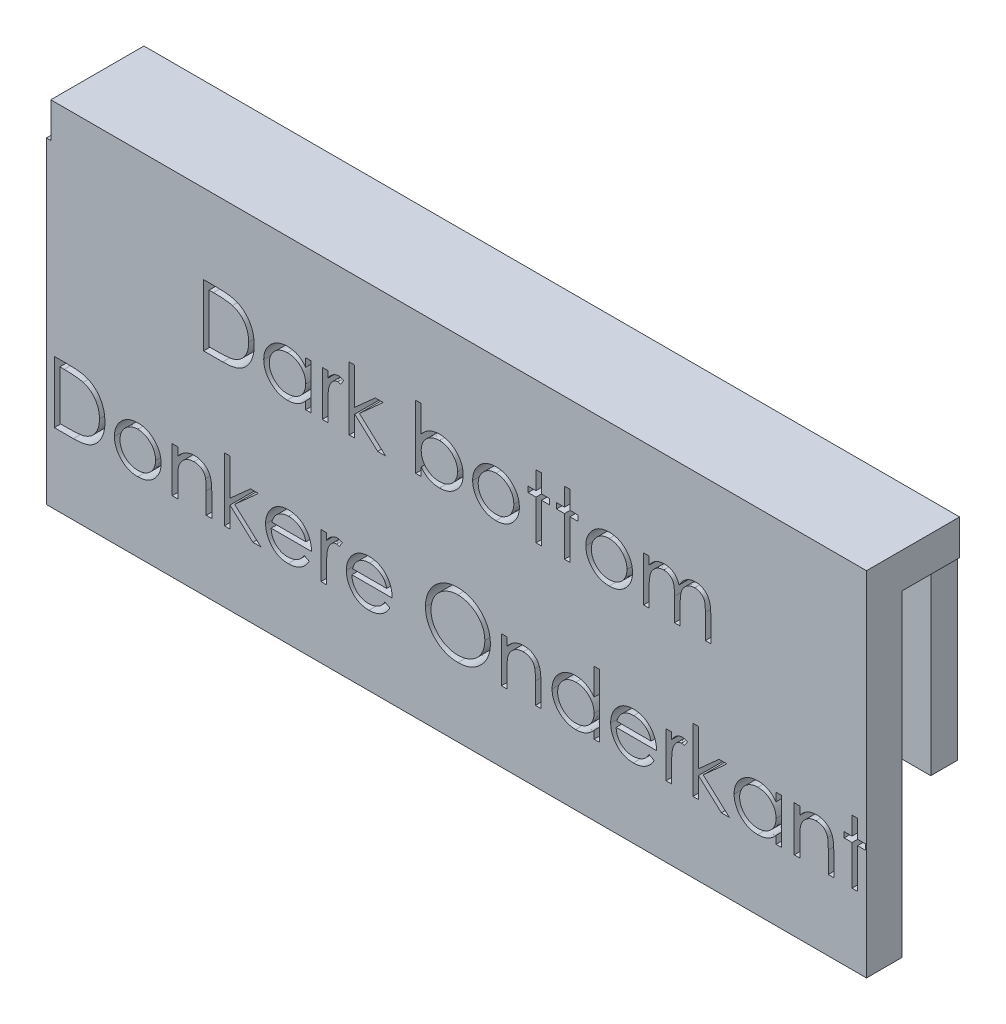
SolidWorks part; units mm, degrees
ref_plane "Front Plane" through (0, 0, 0) normal (0, 0, 1) x (1, 0, 0)
ref_plane "Top Plane" through (0, 0, 0) normal (0, 1, 0) x (1, 0, 0)
ref_plane "Right Plane" through (0, 0, 0) normal (1, 0, 0) x (0, 0, -1)
sketch "Sketch1" plane through (0, 0, 0) normal (0, 0, 1) x (1, 0, 0)
  line L0 (61.5, 25) -> (3, 25) construction
  line L1 (9, 25) -> (55.5, 25)
  line L2 (9, 25) -> (9, 7)
  line L3 (9, 7) -> (55.5, 7)
  line L4 (55.5, 25) -> (55.5, 7)
  line L5 (55.5, 15) -> (55.5, 25) construction
  line L6 (9, 15) -> (9, 25) construction
  line L7 (2, 2) -> (62.5, 2) construction
  dimension "D1" = 5
extrude "Boss-Extrude1" add sketch "Sketch1" along normal blind 2
sketch "Sketch3" plane through (0, 15, 0) normal (0, 1, 0) x (1, 0, 0)
  line L0 (9.2511, 3.2803) -> (9.2511, 1.7537)
  line L5 (9.2511, 1.7537) -> (55.39, 1.7537)
  line L6 (55.39, 3.2803) -> (55.39, 1.7537)
  line L7 (9.2511, 3.2803) -> (55.39, 3.2803)
extrude "Boss-Extrude2" add sketch "Sketch3" along normal up to surface (10 mm away) separate body
sketch "Sketch4" plane through (0, 25, 0) normal (0, 1, 0) x (1, 0, 0)
  line L1 (9.2511, 3.2803) -> (55.5, 3.2803)
  line L2 (9.2511, 3.2803) -> (9.2511, -2)
  line L3 (9.2511, -2) -> (55.5, -2)
  line L4 (55.5, 3.2803) -> (55.5, -2)
extrude "Boss-Extrude3" add sketch "Sketch4" along normal blind 2
sketch "Sketch5" plane through (0, 0, 2) normal (0, 0, 1) x (1, 0, 0)
  line L0 (9, 19) -> (55.5, 19) construction
  line L1 (9, 25) -> (9, 7) construction
  line L2 (55.5, 7) -> (55.5, 27) construction
  line L3 (9.2511, 27) -> (55.5, 27) construction
  line L4 (9, 11) -> (55.5, 11) construction
  line L302 (17.9135, 19) -> (17.9135, 22.5)
  line L303 (17.9135, 22.5) -> (18.6202, 22.5)
  line L304 (18.9981, 19) -> (17.9135, 19)
  line L305 (18.2276, 19.359) -> (18.6293, 19.359)
  line L306 (18.4737, 22.141) -> (18.2276, 22.141)
  line L307 (18.2276, 22.141) -> (18.2276, 19.359)
  line L308 (24.016, 21.5577) -> (24.016, 19)
  line L309 (24.016, 19) -> (23.7019, 19)
  line L310 (23.7019, 19) -> (23.7019, 19.4424)
  line L311 (23.7019, 21.0844) -> (23.7019, 21.5577)
  line L312 (23.7019, 21.5577) -> (24.016, 21.5577)
  line L313 (24.6442, 21.5577) -> (24.9583, 21.5577)
  line L314 (24.9583, 21.5577) -> (24.9583, 21.1812)
  line L315 (25.8558, 21.5149) -> (25.6833, 21.2429)
  line L316 (24.9583, 19.8596) -> (24.9583, 19)
  line L317 (24.9583, 19) -> (24.6442, 19)
  line L318 (24.6442, 19) -> (24.6442, 21.5577)
  line L319 (26.1699, 22.5897) -> (26.484, 22.5897)
  line L320 (26.484, 22.5897) -> (26.484, 20.5144)
  line L321 (26.484, 20.5144) -> (27.6478, 21.5577)
  line L322 (27.6478, 21.5577) -> (28.0994, 21.5577)
  line L323 (28.0994, 21.5577) -> (26.749, 20.3462)
  line L324 (26.749, 20.3462) -> (28.234, 19)
  line L325 (28.234, 19) -> (27.7832, 19)
  line L326 (27.7832, 19) -> (26.484, 20.1786)
  line L327 (26.484, 20.1786) -> (26.484, 19)
  line L328 (26.484, 19) -> (26.1699, 19)
  line L329 (26.1699, 19) -> (26.1699, 22.5897)
  line L330 (29.9391, 19) -> (29.9391, 22.5897)
  line L331 (29.9391, 22.5897) -> (30.2532, 22.5897)
  line L332 (30.2532, 22.5897) -> (30.2532, 21.0935)
  line L333 (30.2532, 19.4733) -> (30.2532, 19)
  line L334 (30.2532, 19) -> (29.9391, 19)
  line L335 (36.7596, 22.5897) -> (37.0737, 22.5897)
  line L336 (37.0737, 22.5897) -> (37.0737, 21.5577)
  line L337 (37.0737, 21.5577) -> (37.5224, 21.5577)
  line L338 (37.5224, 21.5577) -> (37.5224, 21.2436)
  line L339 (37.5224, 21.2436) -> (37.0737, 21.2436)
  line L340 (37.0737, 21.2436) -> (37.0737, 19)
  line L341 (37.0737, 19) -> (36.7596, 19)
  line L342 (36.7596, 19) -> (36.7596, 21.2436)
  line L343 (36.7596, 21.2436) -> (36.3109, 21.2436)
  line L344 (36.3109, 21.2436) -> (36.3109, 21.5577)
  line L345 (36.3109, 21.5577) -> (36.7596, 21.5577)
  line L346 (36.7596, 21.5577) -> (36.7596, 22.5897)
  line L347 (38.375, 22.5897) -> (38.6891, 22.5897)
  line L348 (38.6891, 22.5897) -> (38.6891, 21.5577)
  line L349 (38.6891, 21.5577) -> (39.1378, 21.5577)
  line L350 (39.1378, 21.5577) -> (39.1378, 21.2436)
  line L351 (39.1378, 21.2436) -> (38.6891, 21.2436)
  line L352 (38.6891, 21.2436) -> (38.6891, 19)
  line L353 (38.6891, 19) -> (38.375, 19)
  line L354 (38.375, 19) -> (38.375, 21.2436)
  line L355 (38.375, 21.2436) -> (37.9263, 21.2436)
  line L356 (37.9263, 21.2436) -> (37.9263, 21.5577)
  line L357 (37.9263, 21.5577) -> (38.375, 21.5577)
  line L358 (38.375, 21.5577) -> (38.375, 22.5897)
  line L359 (42.8622, 21.5577) -> (43.1763, 21.5577)
  line L360 (43.1763, 21.5577) -> (43.1763, 21.1132)
  line L361 (46.6763, 20.3854) -> (46.6763, 19)
  line L362 (46.6763, 19) -> (46.3622, 19)
  line L363 (46.3622, 19) -> (46.3622, 20.3868)
  line L364 (44.9263, 19.9949) -> (44.9263, 19)
  line L365 (44.9263, 19) -> (44.6122, 19)
  line L366 (44.6122, 19) -> (44.6122, 20.3006)
  line L367 (43.1763, 20.0762) -> (43.1763, 19)
  line L368 (43.1763, 19) -> (42.8622, 19)
  line L369 (42.8622, 19) -> (42.8622, 21.5577)
  line L370 (9.4487, 11) -> (9.4487, 14.5)
  line L371 (9.4487, 14.5) -> (10.1554, 14.5)
  line L372 (10.5334, 11) -> (9.4487, 11)
  line L373 (9.7628, 11.359) -> (10.1646, 11.359)
  line L374 (10.0089, 14.141) -> (9.7628, 14.141)
  line L375 (9.7628, 14.141) -> (9.7628, 11.359)
  line L376 (16.1346, 13.5577) -> (16.4487, 13.5577)
  line L377 (16.4487, 13.5577) -> (16.4487, 13.0964)
  line L378 (18.3782, 12.3062) -> (18.3782, 11)
  line L379 (18.3782, 11) -> (18.0641, 11)
  line L380 (18.0641, 11) -> (18.0641, 12.2031)
  line L381 (16.4487, 11.9248) -> (16.4487, 11)
  line L382 (16.4487, 11) -> (16.1346, 11)
  line L383 (16.1346, 11) -> (16.1346, 13.5577)
  line L384 (19.0962, 14.5897) -> (19.4103, 14.5897)
  line L385 (19.4103, 14.5897) -> (19.4103, 12.5144)
  line L386 (19.4103, 12.5144) -> (20.5741, 13.5577)
  line L387 (20.5741, 13.5577) -> (21.0256, 13.5577)
  line L388 (21.0256, 13.5577) -> (19.6753, 12.3462)
  line L389 (19.6753, 12.3462) -> (21.1603, 11)
  line L390 (21.1603, 11) -> (20.7094, 11)
  line L391 (20.7094, 11) -> (19.4103, 12.1786)
  line L392 (19.4103, 12.1786) -> (19.4103, 11)
  line L393 (19.4103, 11) -> (19.0962, 11)
  line L394 (19.0962, 11) -> (19.0962, 14.5897)
  line L395 (23.6184, 11.8077) -> (23.8974, 11.6612)
  line L396 (24.0321, 12.2115) -> (21.7436, 12.2115)
  line L397 (21.7765, 12.5256) -> (23.7179, 12.5256)
  line L398 (24.5705, 13.5577) -> (24.8846, 13.5577)
  line L399 (24.8846, 13.5577) -> (24.8846, 13.1812)
  line L400 (25.7821, 13.5149) -> (25.6096, 13.2429)
  line L401 (24.8846, 11.8596) -> (24.8846, 11)
  line L402 (24.8846, 11) -> (24.5705, 11)
  line L403 (24.5705, 11) -> (24.5705, 13.5577)
  line L404 (28.1953, 11.8077) -> (28.4744, 11.6612)
  line L405 (28.609, 12.2115) -> (26.3205, 12.2115)
  line L406 (26.3535, 12.5256) -> (28.2949, 12.5256)
  line L407 (34.8013, 13.5577) -> (35.1154, 13.5577)
  line L408 (35.1154, 13.5577) -> (35.1154, 13.0964)
  line L409 (37.0449, 12.3062) -> (37.0449, 11)
  line L410 (37.0449, 11) -> (36.7308, 11)
  line L411 (36.7308, 11) -> (36.7308, 12.2031)
  line L412 (35.1154, 11.9248) -> (35.1154, 11)
  line L413 (35.1154, 11) -> (34.8013, 11)
  line L414 (34.8013, 11) -> (34.8013, 13.5577)
  line L415 (40.3654, 14.5897) -> (40.3654, 11)
  line L416 (40.3654, 11) -> (40.0513, 11)
  line L417 (40.0513, 11) -> (40.0513, 11.4424)
  line L418 (40.0513, 13.0627) -> (40.0513, 14.5897)
  line L419 (40.0513, 14.5897) -> (40.3654, 14.5897)
  line L420 (43.1825, 11.8077) -> (43.4615, 11.6612)
  line L421 (43.5962, 12.2115) -> (41.3077, 12.2115)
  line L422 (41.3406, 12.5256) -> (43.2821, 12.5256)
  line L423 (44.1346, 13.5577) -> (44.4487, 13.5577)
  line L424 (44.4487, 13.5577) -> (44.4487, 13.1812)
  line L425 (45.3462, 13.5149) -> (45.1737, 13.2429)
  line L426 (44.4487, 11.8596) -> (44.4487, 11)
  line L427 (44.4487, 11) -> (44.1346, 11)
  line L428 (44.1346, 11) -> (44.1346, 13.5577)
  line L429 (45.6603, 14.5897) -> (45.9744, 14.5897)
  line L430 (45.9744, 14.5897) -> (45.9744, 12.5144)
  line L431 (45.9744, 12.5144) -> (47.1382, 13.5577)
  line L432 (47.1382, 13.5577) -> (47.5897, 13.5577)
  line L433 (47.5897, 13.5577) -> (46.2394, 12.3462)
  line L434 (46.2394, 12.3462) -> (47.7244, 11)
  line L435 (47.7244, 11) -> (47.2735, 11)
  line L436 (47.2735, 11) -> (45.9744, 12.1786)
  line L437 (45.9744, 12.1786) -> (45.9744, 11)
  line L438 (45.9744, 11) -> (45.6603, 11)
  line L439 (45.6603, 11) -> (45.6603, 14.5897)
  line L440 (50.6859, 13.5577) -> (50.6859, 11)
  line L441 (50.6859, 11) -> (50.3718, 11)
  line L442 (50.3718, 11) -> (50.3718, 11.4424)
  line L443 (50.3718, 13.0844) -> (50.3718, 13.5577)
  line L444 (50.3718, 13.5577) -> (50.6859, 13.5577)
  line L445 (51.4038, 13.5577) -> (51.7179, 13.5577)
  line L446 (51.7179, 13.5577) -> (51.7179, 13.0964)
  line L447 (53.6474, 12.3062) -> (53.6474, 11)
  line L448 (53.6474, 11) -> (53.3333, 11)
  line L449 (53.3333, 11) -> (53.3333, 12.2031)
  line L450 (51.7179, 11.9248) -> (51.7179, 11)
  line L451 (51.7179, 11) -> (51.4038, 11)
  line L452 (51.4038, 11) -> (51.4038, 13.5577)
  line L453 (54.6795, 14.5897) -> (54.9936, 14.5897)
  line L454 (54.9936, 14.5897) -> (54.9936, 13.5577)
  line L455 (54.9936, 13.5577) -> (55.4423, 13.5577)
  line L456 (55.4423, 13.5577) -> (55.4423, 13.2436)
  line L457 (55.4423, 13.2436) -> (54.9936, 13.2436)
  line L458 (54.9936, 13.2436) -> (54.9936, 11)
  line L459 (54.9936, 11) -> (54.6795, 11)
  line L460 (54.6795, 11) -> (54.6795, 13.2436)
  line L461 (54.6795, 13.2436) -> (54.2308, 13.2436)
  line L462 (54.2308, 13.2436) -> (54.2308, 13.5577)
  line L463 (54.2308, 13.5577) -> (54.6795, 13.5577)
  line L464 (54.6795, 13.5577) -> (54.6795, 14.5897)
  spline S0 degree 3 poles (18.6202, 22.5) (18.7389, 22.4995) (18.9107, 22.497) (19.1308, 22.4837) (19.2763, 22.4697) (19.4087, 22.4525) (19.56, 22.4254) (19.6658, 22.3968) (19.7308, 22.3738) knots 0 0 0 0 0.317406 0.458844 0.589367 0.707831 0.81577 1 1 1 1
  spline S1 degree 3 poles (19.7308, 22.3738) (19.8115, 22.3452) (19.9284, 22.293) (20.0727, 22.2051) (20.1739, 22.1321) (20.2667, 22.0494) (20.3547, 21.9603) (20.4343, 21.8617) (20.5072, 21.7556) (20.573, 21.6433) (20.6301, 21.525) (20.6775, 21.4012) (20.7169, 21.2724) (20.748, 21.1382) (20.7768, 20.9492) (20.7858, 20.804) (20.7853, 20.7058) knots 0 0 0 0 0.121694 0.181155 0.239875 0.298702 0.357647 0.417605 0.478494 0.540407 0.602345 0.665004 0.728559 0.793651 0.860534 1 1 1 1
  spline S2 degree 3 poles (20.7853, 20.7058) (20.7856, 20.6205) (20.7781, 20.4946) (20.7561, 20.3298) (20.731, 20.2122) (20.7006, 20.0978) (20.6617, 19.988) (20.617, 19.8817) (20.565, 19.7802) (20.5078, 19.6842) (20.4465, 19.5936) (20.3811, 19.5098) (20.3109, 19.4326) (20.2369, 19.362) (20.1586, 19.2975) (20.0757, 19.2404) (19.9887, 19.1883) (19.8951, 19.1429) (19.7929, 19.1044) (19.6819, 19.0726) (19.5622, 19.046) (19.4338, 19.025) (19.2449, 19.0054) (19.0985, 18.9995) (18.9981, 19) knots 0 0 0 0 0.090807 0.134295 0.177024 0.218823 0.260244 0.30108 0.341614 0.381583 0.42012 0.458075 0.494738 0.531195 0.566934 0.602713 0.638327 0.674853 0.713467 0.754442 0.797815 0.843989 0.893072 1 1 1 1
  spline S3 degree 3 poles (18.6293, 19.359) (18.7403, 19.359) (18.9001, 19.3611) (19.1036, 19.3707) (19.2357, 19.3803) (19.354, 19.393) (19.4849, 19.4105) (19.5752, 19.4308) (19.6298, 19.448) knots 0 0 0 0 0.330628 0.475549 0.606746 0.725024 0.829742 1 1 1 1
  spline S4 degree 3 poles (19.6298, 19.448) (19.6931, 19.4695) (19.7863, 19.5053) (19.9005, 19.5701) (19.9806, 19.6235) (20.055, 19.6842) (20.1244, 19.7507) (20.1888, 19.8236) (20.2474, 19.9026) (20.3, 19.9873) (20.3454, 20.0768) (20.3853, 20.1702) (20.4166, 20.2689) (20.4411, 20.372) (20.4647, 20.5179) (20.4712, 20.6304) (20.4712, 20.7065) knots 0 0 0 0 0.123338 0.183125 0.241783 0.300579 0.35968 0.418882 0.479531 0.540851 0.602303 0.664463 0.727806 0.792895 0.859672 1 1 1 1
  spline S5 degree 3 poles (20.4712, 20.7065) (20.4721, 20.787) (20.4637, 20.9055) (20.4384, 21.0593) (20.4117, 21.1683) (20.3775, 21.273) (20.3349, 21.3728) (20.2863, 21.4688) (20.2284, 21.5588) (20.1649, 21.6439) (20.0946, 21.7219) (20.0183, 21.7929) (19.9371, 21.858) (19.8486, 21.9146) (19.722, 21.9832) (19.6192, 22.0211) (19.5492, 22.0429) knots 0 0 0 0 0.137813 0.203226 0.267174 0.330024 0.391794 0.453084 0.514334 0.575 0.634865 0.694116 0.753442 0.813126 0.87408 1 1 1 1
  spline S6 degree 3 poles (19.5492, 22.0429) (19.4872, 22.0616) (19.3857, 22.0829) (19.241, 22.1036) (19.1131, 22.1177) (18.972, 22.1278) (18.7575, 22.1384) (18.5898, 22.1414) (18.4737, 22.141) knots 0 0 0 0 0.179285 0.286583 0.405111 0.535593 0.67819 1 1 1 1
  spline S7 degree 3 poles (23.7019, 19.4424) (23.6347, 19.363) (23.5262, 19.2524) (23.3595, 19.1378) (23.2309, 19.0696) (23.096, 19.0185) (22.9059, 18.9691) (22.7575, 18.9543) (22.6573, 18.9551) knots 0 0 0 0 0.262085 0.38627 0.507165 0.6273 0.748145 1 1 1 1
  spline S8 degree 3 poles (22.6573, 18.9551) (22.5682, 18.9553) (22.436, 18.9668) (22.2659, 19.0077) (22.1446, 19.0496) (22.0289, 19.1052) (21.9179, 19.1717) (21.812, 19.2509) (21.7129, 19.3415) (21.6217, 19.4399) (21.5416, 19.5449) (21.4749, 19.6559) (21.4191, 19.7716) (21.3761, 19.8929) (21.3354, 20.0637) (21.3239, 20.1964) (21.3237, 20.2859) knots 0 0 0 0 0.127433 0.189004 0.24993 0.310668 0.372329 0.434939 0.499576 0.564191 0.626735 0.688109 0.749294 0.810331 0.871901 1 1 1 1
  spline S9 degree 3 poles (21.3237, 20.2859) (21.3242, 20.3737) (21.335, 20.5043) (21.377, 20.672) (21.4205, 20.7914) (21.4763, 20.9057) (21.5442, 21.0151) (21.6243, 21.1199) (21.7165, 21.2176) (21.8165, 21.3078) (21.9234, 21.3862) (22.0346, 21.4539) (22.1519, 21.5076) (22.2734, 21.5509) (22.4446, 21.5916) (22.5777, 21.6018) (22.6671, 21.6026) knots 0 0 0 0 0.126079 0.186904 0.247574 0.308003 0.369132 0.432033 0.496791 0.561611 0.624914 0.686726 0.748079 0.809582 0.871631 1 1 1 1
  spline S10 degree 3 poles (22.6671, 21.6026) (22.7693, 21.6023) (22.921, 21.5891) (23.113, 21.5352) (23.2477, 21.4813) (23.3748, 21.4096) (23.5367, 21.2865) (23.64, 21.1694) (23.7019, 21.0844) knots 0 0 0 0 0.254654 0.376015 0.495255 0.614798 0.738106 1 1 1 1
  spline S11 degree 3 poles (22.6713, 21.2885) (22.5808, 21.2881) (22.4454, 21.273) (22.2744, 21.2165) (22.1534, 21.1593) (22.0408, 21.0872) (21.9401, 21.0001) (21.8505, 20.9003) (21.7752, 20.7882) (21.7139, 20.668) (21.656, 20.5009) (21.6367, 20.3698) (21.6378, 20.2824) knots 0 0 0 0 0.169593 0.252476 0.336244 0.419505 0.502036 0.584775 0.669846 0.754185 0.836658 1 1 1 1
  spline S12 degree 3 poles (21.6378, 20.2824) (21.6386, 20.1954) (21.6552, 20.0639) (21.7151, 19.8971) (21.7763, 19.7759) (21.853, 19.6633) (21.9419, 19.5615) (22.0438, 19.474) (22.1567, 19.4008) (22.2773, 19.3417) (22.4468, 19.2863) (22.5796, 19.2688) (22.6685, 19.2692) knots 0 0 0 0 0.162859 0.245484 0.330807 0.416493 0.499893 0.583048 0.667158 0.751312 0.833785 1 1 1 1
  spline S13 degree 3 poles (22.6685, 19.2692) (22.7588, 19.2696) (22.8944, 19.2852) (23.0672, 19.3413) (23.191, 19.3991) (23.3063, 19.4709) (23.4098, 19.5549) (23.4974, 19.6526) (23.5716, 19.76) (23.6297, 19.8777) (23.6872, 20.0471) (23.7014, 20.1826) (23.7019, 20.2732) knots 0 0 0 0 0.168664 0.252552 0.33824 0.423103 0.505556 0.586176 0.667136 0.748499 0.830452 1 1 1 1
  spline S14 degree 3 poles (23.7019, 20.2732) (23.7017, 20.3428) (23.6929, 20.4458) (23.6617, 20.578) (23.6293, 20.6714) (23.5868, 20.7601) (23.5356, 20.8445) (23.4747, 20.9244) (23.4051, 20.9985) (23.329, 21.0662) (23.2484, 21.1265) (23.1624, 21.1761) (23.0725, 21.2172) (22.9784, 21.2498) (22.8448, 21.2795) (22.7414, 21.2895) (22.6713, 21.2885) knots 0 0 0 0 0.129188 0.191219 0.251913 0.312507 0.373494 0.435152 0.498741 0.562095 0.624187 0.685476 0.746097 0.807612 0.869967 1 1 1 1
  spline S15 degree 3 poles (24.9583, 21.1812) (25.0014, 21.2489) (25.0693, 21.3427) (25.1751, 21.4454) (25.2527, 21.5039) (25.3331, 21.5477) (25.4407, 21.5903) (25.5263, 21.6022) (25.5823, 21.6026) knots 0 0 0 0 0.306112 0.438367 0.560541 0.675317 0.786114 1 1 1 1
  spline S16 degree 3 poles (25.5823, 21.6026) (25.6273, 21.6022) (25.7238, 21.5853) (25.8114, 21.5418) (25.8558, 21.5149) knots 0 0 0 0 0.463523 1 1 1 1
  spline S17 degree 3 poles (25.6833, 21.2429) (25.6547, 21.2556) (25.6032, 21.2788) (25.5474, 21.2881) (25.5227, 21.2885) knots 0 0 0 0 0.56023 1 1 1 1
  spline S18 degree 3 poles (25.5227, 21.2885) (25.4712, 21.2885) (25.3923, 21.2697) (25.2974, 21.2128) (25.2392, 21.1646) (25.1942, 21.1181) (25.162, 21.0774) (25.1326, 21.0318) (25.1044, 20.9821) (25.0787, 20.9274) (25.0459, 20.8463) (25.0263, 20.7819) (25.0144, 20.7374) knots 0 0 0 0 0.191338 0.295191 0.410312 0.47193 0.536425 0.603119 0.674118 0.749332 0.828283 1 1 1 1
  spline S19 degree 3 poles (25.0144, 20.7374) (25.0027, 20.6927) (24.9912, 20.6175) (24.979, 20.5078) (24.9718, 20.4049) (24.9653, 20.2883) (24.96, 20.105) (24.9578, 19.9606) (24.9583, 19.8596) knots 0 0 0 0 0.156938 0.2586 0.375891 0.508166 0.656238 1 1 1 1
  spline S20 degree 3 poles (30.2532, 21.0935) (30.3201, 21.1747) (30.4295, 21.2861) (30.5949, 21.4057) (30.7228, 21.4783) (30.8575, 21.5335) (31.0471, 21.5883) (31.1963, 21.6026) (31.2965, 21.6026) knots 0 0 0 0 0.262681 0.38719 0.50839 0.628966 0.749723 1 1 1 1
  spline S21 degree 3 poles (31.2965, 21.6026) (31.3857, 21.6022) (31.5183, 21.5909) (31.6885, 21.55) (31.8098, 21.5081) (31.9255, 21.4525) (32.0365, 21.386) (32.1424, 21.3068) (32.2415, 21.2162) (32.3328, 21.1178) (32.4127, 21.0126) (32.4802, 20.9022) (32.536, 20.7868) (32.5791, 20.666) (32.6196, 20.4956) (32.6313, 20.3632) (32.6314, 20.2739) knots 0 0 0 0 0.127821 0.189419 0.250372 0.311137 0.372825 0.435463 0.500128 0.564773 0.627344 0.688919 0.749829 0.810578 0.872176 1 1 1 1
  spline S22 degree 3 poles (32.6314, 20.2739) (32.631, 20.1859) (32.62, 20.0549) (32.5783, 19.8866) (32.5344, 19.7669) (32.4791, 19.6519) (32.41, 19.5428) (32.3302, 19.4378) (32.2379, 19.3401) (32.138, 19.2499) (32.0311, 19.1715) (31.9198, 19.1038) (31.8026, 19.0501) (31.681, 19.0068) (31.5096, 18.966) (31.3763, 18.956) (31.2867, 18.9551) knots 0 0 0 0 0.126228 0.187289 0.247869 0.308511 0.369727 0.432536 0.497198 0.561923 0.625133 0.686855 0.748117 0.80953 0.871487 1 1 1 1
  spline S23 degree 3 poles (31.2867, 18.9551) (31.185, 18.9555) (31.0338, 18.9685) (30.8427, 19.0227) (30.7079, 19.0762) (30.5815, 19.1488) (30.4191, 19.2714) (30.3164, 19.389) (30.2532, 19.4733) knots 0 0 0 0 0.25388 0.374863 0.494283 0.614293 0.73697 1 1 1 1
  spline S24 degree 3 poles (31.2839, 19.2692) (31.3744, 19.2696) (31.5097, 19.2846) (31.6808, 19.3412) (31.8017, 19.3984) (31.9144, 19.4705) (32.015, 19.5576) (32.1045, 19.6571) (32.1792, 19.7693) (32.2414, 19.8888) (32.2988, 20.056) (32.3187, 20.1866) (32.3173, 20.2739) knots 0 0 0 0 0.169736 0.252687 0.336526 0.419856 0.502457 0.585265 0.6698 0.754407 0.83695 1 1 1 1
  spline S25 degree 3 poles (32.3173, 20.2739) (32.3162, 20.3612) (32.3006, 20.4936) (32.2392, 20.6605) (32.1781, 20.7816) (32.1022, 20.8946) (32.0132, 20.9961) (31.9113, 21.0837) (31.7985, 21.1567) (31.6783, 21.2162) (31.5094, 21.2711) (31.3772, 21.289) (31.2888, 21.2885) knots 0 0 0 0 0.163805 0.246618 0.331983 0.417466 0.500907 0.584103 0.668254 0.752056 0.83457 1 1 1 1
  spline S26 degree 3 poles (31.2888, 21.2885) (31.1984, 21.289) (31.0633, 21.2711) (30.8898, 21.2159) (30.7655, 21.1571) (30.6497, 21.0849) (30.5461, 21.0002) (30.4567, 20.9034) (30.3832, 20.7949) (30.3248, 20.6777) (30.2681, 20.5088) (30.2536, 20.3742) (30.2532, 20.2838) knots 0 0 0 0 0.168182 0.252419 0.338618 0.424014 0.506402 0.587545 0.668801 0.7501 0.831022 1 1 1 1
  spline S27 degree 3 poles (30.2532, 20.2838) (30.2534, 20.2142) (30.2623, 20.1112) (30.2935, 19.979) (30.3258, 19.8856) (30.3683, 19.7969) (30.4195, 19.7124) (30.4804, 19.6328) (30.5494, 19.5583) (30.6253, 19.4905) (30.7068, 19.4317) (30.7923, 19.3811) (30.8825, 19.3408) (30.9767, 19.3079) (31.1103, 19.2783) (31.2137, 19.2682) (31.2839, 19.2692) knots 0 0 0 0 0.129212 0.191253 0.251958 0.312564 0.373562 0.43523 0.498536 0.561901 0.624098 0.685023 0.746051 0.807577 0.869943 1 1 1 1
  spline S28 degree 3 poles (34.495, 21.6026) (34.5891, 21.6035) (34.7283, 21.59) (34.9064, 21.5453) (35.0322, 21.5001) (35.1506, 21.4394) (35.303, 21.3418) (35.4046, 21.2491) (35.4667, 21.1812) knots 0 0 0 0 0.258332 0.382134 0.503804 0.624693 0.746871 1 1 1 1
  spline S29 degree 3 poles (35.4667, 21.1812) (35.5238, 21.1189) (35.6002, 21.0189) (35.6824, 20.8746) (35.7315, 20.7623) (35.7702, 20.646) (35.8073, 20.483) (35.8168, 20.3568) (35.8173, 20.2718) knots 0 0 0 0 0.253834 0.376506 0.498534 0.621368 0.744565 1 1 1 1
  spline S30 degree 3 poles (35.8173, 20.2718) (35.8178, 20.1863) (35.8061, 20.0591) (35.7675, 19.8948) (35.7267, 19.7769) (35.6743, 19.663) (35.6104, 19.5536) (35.5346, 19.4485) (35.4486, 19.3485) (35.3535, 19.2563) (35.2504, 19.176) (35.1412, 19.1071) (35.0246, 19.0517) (34.9015, 19.008) (34.7255, 18.9662) (34.5879, 18.9555) (34.495, 18.9551) knots 0 0 0 0 0.123337 0.183265 0.243172 0.302898 0.363774 0.425605 0.489659 0.553785 0.616222 0.677854 0.739517 0.802097 0.865866 1 1 1 1
  spline S31 degree 3 poles (34.495, 18.9551) (34.4016, 18.9556) (34.2636, 18.966) (34.087, 19.008) (33.9638, 19.0518) (33.8467, 19.1071) (33.7369, 19.1757) (33.6337, 19.2563) (33.5386, 19.3484) (33.4526, 19.4485) (33.3767, 19.5536) (33.3129, 19.663) (33.2605, 19.7769) (33.2197, 19.8948) (33.1811, 20.0591) (33.1694, 20.1863) (33.1699, 20.2718) knots 0 0 0 0 0.134635 0.198324 0.260825 0.322714 0.384555 0.446913 0.510958 0.574931 0.636685 0.697483 0.757134 0.816966 0.876818 1 1 1 1
  spline S32 degree 3 poles (33.1699, 20.2718) (33.1704, 20.3565) (33.1799, 20.4825) (33.2169, 20.645) (33.2556, 20.761) (33.3052, 20.8727) (33.3863, 21.0175) (33.464, 21.1166) (33.5204, 21.1791) knots 0 0 0 0 0.255238 0.378679 0.501088 0.622714 0.746241 1 1 1 1
  spline S33 degree 3 poles (33.5204, 21.1791) (33.5821, 21.2479) (33.6846, 21.3398) (33.8366, 21.4393) (33.9563, 21.4988) (34.082, 21.5456) (34.2608, 21.5899) (34.4004, 21.6034) (34.495, 21.6026) knots 0 0 0 0 0.252713 0.374819 0.496436 0.617911 0.741288 1 1 1 1
  spline S34 degree 3 poles (34.4936, 21.2885) (34.4266, 21.2883) (34.3271, 21.2792) (34.1991, 21.2481) (34.1077, 21.2156) (34.02, 21.1735) (33.9361, 21.1218) (33.8557, 21.0611) (33.7803, 20.9917) (33.7111, 20.9158) (33.6506, 20.8349) (33.5992, 20.7504) (33.5564, 20.6622) (33.5245, 20.5693) (33.493, 20.4391) (33.4842, 20.3379) (33.484, 20.2697) knots 0 0 0 0 0.126044 0.187165 0.247399 0.30838 0.36978 0.432584 0.497641 0.562401 0.625557 0.687332 0.748313 0.809791 0.871768 1 1 1 1
  spline S35 degree 3 poles (33.484, 20.2697) (33.4842, 20.181) (33.4998, 20.0477) (33.5581, 19.8798) (33.6167, 19.7601) (33.6901, 19.6495) (33.7766, 19.5508) (33.8752, 19.4656) (33.9848, 19.3949) (34.1032, 19.3388) (34.2716, 19.285) (34.4043, 19.2682) (34.4936, 19.2692) knots 0 0 0 0 0.168179 0.251488 0.335841 0.419834 0.502345 0.583649 0.665931 0.748717 0.831047 1 1 1 1
  spline S36 degree 3 poles (34.4936, 19.2692) (34.5829, 19.2683) (34.7154, 19.2847) (34.8835, 19.339) (35.0017, 19.3949) (35.1113, 19.4659) (35.2106, 19.5503) (35.2964, 19.6497) (35.3697, 19.7603) (35.4292, 19.8796) (35.4872, 20.0478) (35.503, 20.181) (35.5032, 20.2697) knots 0 0 0 0 0.168983 0.250908 0.333708 0.416005 0.49766 0.579893 0.663902 0.748466 0.831791 1 1 1 1
  spline S37 degree 3 poles (35.5032, 20.2697) (35.503, 20.3379) (35.4941, 20.4391) (35.4627, 20.5693) (35.4308, 20.6621) (35.3881, 20.7506) (35.3357, 20.8347) (35.2755, 20.9161) (35.2054, 20.9914) (35.1301, 21.0611) (35.0497, 21.1218) (34.9659, 21.1732) (34.8785, 21.2159) (34.7871, 21.2478) (34.6595, 21.2795) (34.5603, 21.2881) (34.4936, 21.2885) knots 0 0 0 0 0.128274 0.19027 0.251768 0.312769 0.374793 0.43797 0.503047 0.568125 0.63095 0.692369 0.752973 0.813641 0.874355 1 1 1 1
  spline S38 degree 3 poles (40.9117, 21.6026) (41.0057, 21.6035) (41.145, 21.59) (41.3231, 21.5453) (41.4489, 21.5001) (41.5673, 21.4394) (41.7196, 21.3418) (41.8213, 21.2491) (41.8834, 21.1812) knots 0 0 0 0 0.258332 0.382134 0.503804 0.624693 0.746871 1 1 1 1
  spline S39 degree 3 poles (41.8834, 21.1812) (41.9404, 21.1189) (42.0168, 21.0189) (42.0991, 20.8746) (42.1482, 20.7623) (42.1868, 20.646) (42.224, 20.483) (42.2335, 20.3568) (42.234, 20.2718) knots 0 0 0 0 0.253834 0.376506 0.498534 0.621368 0.744565 1 1 1 1
  spline S40 degree 3 poles (42.234, 20.2718) (42.2345, 20.1863) (42.2228, 20.0591) (42.1841, 19.8948) (42.1434, 19.7769) (42.091, 19.663) (42.0271, 19.5536) (41.9512, 19.4485) (41.8652, 19.3485) (41.7702, 19.2563) (41.6671, 19.176) (41.5579, 19.1071) (41.4413, 19.0517) (41.3182, 19.008) (41.1421, 18.9662) (41.0046, 18.9555) (40.9117, 18.9551) knots 0 0 0 0 0.123337 0.183265 0.243172 0.302898 0.363774 0.425605 0.489659 0.553785 0.616222 0.677854 0.739517 0.802097 0.865866 1 1 1 1
  spline S41 degree 3 poles (40.9117, 18.9551) (40.8183, 18.9556) (40.6802, 18.966) (40.5037, 19.008) (40.3805, 19.0518) (40.2633, 19.1071) (40.1536, 19.1757) (40.0504, 19.2563) (39.9553, 19.3484) (39.8693, 19.4485) (39.7934, 19.5536) (39.7295, 19.663) (39.6772, 19.7769) (39.6364, 19.8948) (39.5977, 20.0591) (39.586, 20.1863) (39.5865, 20.2718) knots 0 0 0 0 0.134635 0.198324 0.260825 0.322714 0.384555 0.446913 0.510958 0.574931 0.636685 0.697483 0.757134 0.816966 0.876818 1 1 1 1
  spline S42 degree 3 poles (39.5865, 20.2718) (39.587, 20.3565) (39.5966, 20.4825) (39.6336, 20.645) (39.6723, 20.761) (39.7218, 20.8727) (39.803, 21.0175) (39.8807, 21.1166) (39.9371, 21.1791) knots 0 0 0 0 0.255238 0.378679 0.501088 0.622714 0.746241 1 1 1 1
  spline S43 degree 3 poles (39.9371, 21.1791) (39.9987, 21.2479) (40.1012, 21.3398) (40.2532, 21.4393) (40.3729, 21.4988) (40.4986, 21.5456) (40.6775, 21.5899) (40.8171, 21.6034) (40.9117, 21.6026) knots 0 0 0 0 0.252713 0.374819 0.496436 0.617911 0.741288 1 1 1 1
  spline S44 degree 3 poles (40.9103, 21.2885) (40.8433, 21.2883) (40.7437, 21.2792) (40.6158, 21.2481) (40.5243, 21.2156) (40.4367, 21.1735) (40.3528, 21.1218) (40.2723, 21.0611) (40.197, 20.9917) (40.1278, 20.9158) (40.0673, 20.8349) (40.0159, 20.7504) (39.973, 20.6622) (39.9412, 20.5693) (39.9097, 20.4391) (39.9008, 20.3379) (39.9006, 20.2697) knots 0 0 0 0 0.126044 0.187165 0.247399 0.30838 0.36978 0.432584 0.497641 0.562401 0.625557 0.687332 0.748313 0.809791 0.871768 1 1 1 1
  spline S45 degree 3 poles (39.9006, 20.2697) (39.9009, 20.181) (39.9165, 20.0477) (39.9748, 19.8798) (40.0333, 19.7601) (40.1068, 19.6495) (40.1932, 19.5508) (40.2919, 19.4656) (40.4015, 19.3949) (40.5199, 19.3388) (40.6882, 19.285) (40.821, 19.2682) (40.9103, 19.2692) knots 0 0 0 0 0.168179 0.251488 0.335841 0.419834 0.502345 0.583649 0.665931 0.748717 0.831047 1 1 1 1
  spline S46 degree 3 poles (40.9103, 19.2692) (40.9995, 19.2683) (41.1321, 19.2847) (41.3001, 19.339) (41.4184, 19.3949) (41.5279, 19.4659) (41.6273, 19.5503) (41.713, 19.6497) (41.7864, 19.7603) (41.8459, 19.8796) (41.9039, 20.0478) (41.9197, 20.181) (41.9199, 20.2697) knots 0 0 0 0 0.168983 0.250908 0.333708 0.416005 0.49766 0.579893 0.663902 0.748466 0.831791 1 1 1 1
  spline S47 degree 3 poles (41.9199, 20.2697) (41.9197, 20.3379) (41.9108, 20.4391) (41.8794, 20.5693) (41.8474, 20.6621) (41.8048, 20.7506) (41.7524, 20.8347) (41.6921, 20.9161) (41.6221, 20.9914) (41.5468, 21.0611) (41.4663, 21.1218) (41.3826, 21.1732) (41.2952, 21.2159) (41.2037, 21.2478) (41.0762, 21.2795) (40.977, 21.2881) (40.9103, 21.2885) knots 0 0 0 0 0.128274 0.19027 0.251768 0.312769 0.374793 0.43797 0.503047 0.568125 0.63095 0.692369 0.752973 0.813641 0.874355 1 1 1 1
  spline S48 degree 3 poles (43.1763, 21.1132) (43.229, 21.1886) (43.3354, 21.3215) (43.4654, 21.4316) (43.531, 21.4729) knots 0 0 0 0 0.543395 1 1 1 1
  spline S49 degree 3 poles (43.531, 21.4729) (43.6126, 21.515) (43.7845, 21.5817) (43.9676, 21.6019) (44.0583, 21.6026) knots 0 0 0 0 0.503035 1 1 1 1
  spline S50 degree 3 poles (44.0583, 21.6026) (44.1194, 21.6018) (44.211, 21.594) (44.3288, 21.5627) (44.4134, 21.5303) (44.4931, 21.4911) (44.5662, 21.445) (44.6318, 21.3933) (44.6899, 21.3336) (44.7422, 21.2643) (44.8099, 21.1505) (44.8487, 21.0535) (44.8723, 20.9849) knots 0 0 0 0 0.166532 0.248836 0.331246 0.412957 0.490494 0.566156 0.639987 0.716765 0.802144 1 1 1 1
  spline S51 degree 3 poles (44.8723, 20.9849) (44.8984, 21.034) (44.9414, 21.1044) (45.0058, 21.1915) (45.0558, 21.2515) (45.1082, 21.3068) (45.1633, 21.3576) (45.2207, 21.4041) (45.3005, 21.4585) (45.4043, 21.5161) (45.5788, 21.5832) (45.718, 21.6028) (45.8104, 21.6026) knots 0 0 0 0 0.141226 0.209116 0.27484 0.339483 0.402476 0.464942 0.526833 0.647415 0.765562 1 1 1 1
  spline S52 degree 3 poles (45.8104, 21.6026) (45.8941, 21.6019) (46.0191, 21.5882) (46.1733, 21.5302) (46.2788, 21.472) (46.374, 21.3988) (46.4567, 21.3118) (46.5264, 21.2114) (46.572, 21.117) (46.6029, 21.0337) (46.622, 20.9627) (46.6388, 20.8845) (46.6528, 20.7992) (46.663, 20.7062) (46.6736, 20.5677) (46.6767, 20.4598) (46.6763, 20.3854) knots 0 0 0 0 0.147965 0.218797 0.28947 0.359724 0.429708 0.500497 0.574429 0.613947 0.657155 0.703973 0.754939 0.809707 0.868833 1 1 1 1
  spline S53 degree 3 poles (46.3622, 20.3868) (46.3623, 20.4497) (46.3613, 20.54) (46.3542, 20.6549) (46.3482, 20.7291) (46.34, 20.7954) (46.3294, 20.8536) (46.3181, 20.9042) (46.2993, 20.9602) (46.2694, 21.0221) (46.2238, 21.0888) (46.1663, 21.1469) (46.0999, 21.1973) (46.0244, 21.2383) (45.9105, 21.2785) (45.8182, 21.2889) (45.7557, 21.2885) knots 0 0 0 0 0.150563 0.216151 0.27568 0.328707 0.375904 0.417302 0.452693 0.517265 0.581217 0.645322 0.712024 0.78013 0.850218 1 1 1 1
  spline S54 degree 3 poles (45.7557, 21.2885) (45.6772, 21.2898) (45.5602, 21.2705) (45.4132, 21.2125) (45.311, 21.1502) (45.217, 21.0753) (45.1361, 20.9864) (45.0692, 20.8858) (45.024, 20.7926) (44.9954, 20.709) (44.9765, 20.6359) (44.9618, 20.5528) (44.9481, 20.4603) (44.9391, 20.3577) (44.9277, 20.2017) (44.9268, 20.0795) (44.9263, 19.9949) knots 0 0 0 0 0.134707 0.201865 0.270788 0.340024 0.408083 0.476813 0.547346 0.58564 0.628865 0.677153 0.730803 0.789807 0.854325 1 1 1 1
  spline S55 degree 3 poles (44.6122, 20.3006) (44.6122, 20.3712) (44.6113, 20.4725) (44.6042, 20.6012) (44.5983, 20.684) (44.5898, 20.7574) (44.5802, 20.8218) (44.5689, 20.877) (44.5501, 20.9376) (44.5214, 21.0043) (44.4752, 21.0755) (44.4176, 21.1377) (44.35, 21.1909) (44.274, 21.2348) (44.1596, 21.2781) (44.0663, 21.2879) (44.0036, 21.2885) knots 0 0 0 0 0.158779 0.227738 0.289946 0.345499 0.393896 0.436374 0.472122 0.536384 0.599078 0.661948 0.726311 0.791771 0.858647 1 1 1 1
  spline S56 degree 3 poles (44.0036, 21.2885) (43.9278, 21.2891) (43.8139, 21.2709) (43.671, 21.2134) (43.5691, 21.1538) (43.4754, 21.0799) (43.3934, 20.993) (43.3245, 20.8941) (43.2787, 20.8019) (43.2492, 20.7204) (43.2296, 20.651) (43.2128, 20.574) (43.2003, 20.4891) (43.1882, 20.3969) (43.18, 20.2584) (43.1753, 20.1506) (43.1763, 20.0762) knots 0 0 0 0 0.136871 0.206114 0.277538 0.349772 0.421251 0.492911 0.567027 0.606614 0.649704 0.697303 0.749086 0.804881 0.865485 1 1 1 1
  spline S57 degree 3 poles (10.1554, 14.5) (10.2742, 14.4995) (10.4459, 14.497) (10.6661, 14.4837) (10.8115, 14.4697) (10.944, 14.4525) (11.0953, 14.4254) (11.201, 14.3968) (11.266, 14.3738) knots 0 0 0 0 0.317406 0.458844 0.589367 0.707831 0.81577 1 1 1 1
  spline S58 degree 3 poles (11.266, 14.3738) (11.3467, 14.3452) (11.4636, 14.293) (11.6079, 14.2051) (11.7091, 14.1321) (11.8019, 14.0494) (11.89, 13.9603) (11.9696, 13.8617) (12.0425, 13.7556) (12.1082, 13.6433) (12.1654, 13.525) (12.2128, 13.4012) (12.2522, 13.2724) (12.2832, 13.1382) (12.3121, 12.9492) (12.321, 12.804) (12.3205, 12.7058) knots 0 0 0 0 0.121694 0.181155 0.239875 0.298702 0.357647 0.417605 0.478494 0.540407 0.602345 0.665004 0.728559 0.793651 0.860534 1 1 1 1
  spline S59 degree 3 poles (12.3205, 12.7058) (12.3209, 12.6205) (12.3133, 12.4946) (12.2913, 12.3298) (12.2663, 12.2122) (12.2359, 12.0978) (12.1969, 11.988) (12.1523, 11.8817) (12.1002, 11.7802) (12.0431, 11.6842) (11.9818, 11.5936) (11.9163, 11.5098) (11.8462, 11.4326) (11.7722, 11.362) (11.6938, 11.2975) (11.611, 11.2404) (11.524, 11.1883) (11.4303, 11.1429) (11.3282, 11.1044) (11.2172, 11.0726) (11.0975, 11.046) (10.969, 11.025) (10.7802, 11.0054) (10.6337, 10.9995) (10.5334, 11) knots 0 0 0 0 0.090807 0.134295 0.177024 0.218823 0.260244 0.30108 0.341614 0.381583 0.42012 0.458075 0.494738 0.531195 0.566934 0.602713 0.638327 0.674853 0.713467 0.754442 0.797815 0.843989 0.893072 1 1 1 1
  spline S60 degree 3 poles (10.1646, 11.359) (10.2756, 11.359) (10.4353, 11.3611) (10.6389, 11.3707) (10.771, 11.3803) (10.8893, 11.393) (11.0202, 11.4105) (11.1105, 11.4308) (11.1651, 11.448) knots 0 0 0 0 0.330628 0.475549 0.606746 0.725024 0.829742 1 1 1 1
  spline S61 degree 3 poles (11.1651, 11.448) (11.2283, 11.4695) (11.3215, 11.5053) (11.4358, 11.5701) (11.5159, 11.6235) (11.5902, 11.6842) (11.6596, 11.7507) (11.724, 11.8236) (11.7827, 11.9026) (11.8352, 11.9873) (11.8807, 12.0768) (11.9205, 12.1702) (11.9518, 12.2689) (11.9763, 12.372) (12, 12.5179) (12.0064, 12.6304) (12.0064, 12.7065) knots 0 0 0 0 0.123338 0.183125 0.241783 0.300579 0.35968 0.418882 0.479531 0.540851 0.602303 0.664463 0.727806 0.792895 0.859672 1 1 1 1
  spline S62 degree 3 poles (12.0064, 12.7065) (12.0073, 12.787) (11.999, 12.9055) (11.9737, 13.0593) (11.9469, 13.1683) (11.9128, 13.273) (11.8702, 13.3728) (11.8215, 13.4688) (11.7636, 13.5588) (11.7002, 13.6439) (11.6298, 13.7219) (11.5536, 13.7929) (11.4724, 13.858) (11.3838, 13.9146) (11.2572, 13.9832) (11.1545, 14.0211) (11.0844, 14.0429) knots 0 0 0 0 0.137813 0.203226 0.267174 0.330024 0.391794 0.453084 0.514334 0.575 0.634865 0.694116 0.753442 0.813126 0.87408 1 1 1 1
  spline S63 degree 3 poles (11.0844, 14.0429) (11.0224, 14.0616) (10.921, 14.0829) (10.7762, 14.1036) (10.6483, 14.1177) (10.5073, 14.1278) (10.2928, 14.1384) (10.1251, 14.1414) (10.0089, 14.141) knots 0 0 0 0 0.179285 0.286583 0.405111 0.535593 0.67819 1 1 1 1
  spline S64 degree 3 poles (14.1841, 13.6026) (14.2782, 13.6035) (14.4174, 13.59) (14.5955, 13.5453) (14.7213, 13.5001) (14.8397, 13.4394) (14.9921, 13.3418) (15.0937, 13.2491) (15.1558, 13.1812) knots 0 0 0 0 0.258332 0.382134 0.503804 0.624693 0.746871 1 1 1 1
  spline S65 degree 3 poles (15.1558, 13.1812) (15.2129, 13.1189) (15.2893, 13.0189) (15.3715, 12.8746) (15.4206, 12.7623) (15.4593, 12.646) (15.4965, 12.483) (15.5059, 12.3568) (15.5064, 12.2718) knots 0 0 0 0 0.253834 0.376506 0.498534 0.621368 0.744565 1 1 1 1
  spline S66 degree 3 poles (15.5064, 12.2718) (15.5069, 12.1863) (15.4952, 12.0591) (15.4566, 11.8948) (15.4158, 11.7769) (15.3634, 11.663) (15.2995, 11.5536) (15.2237, 11.4485) (15.1377, 11.3485) (15.0426, 11.2563) (14.9395, 11.176) (14.8303, 11.1071) (14.7137, 11.0517) (14.5906, 11.008) (14.4146, 10.9662) (14.277, 10.9555) (14.1841, 10.9551) knots 0 0 0 0 0.123337 0.183265 0.243172 0.302898 0.363774 0.425605 0.489659 0.553785 0.616222 0.677854 0.739517 0.802097 0.865866 1 1 1 1
  spline S67 degree 3 poles (14.1841, 10.9551) (14.0907, 10.9556) (13.9527, 10.966) (13.7762, 11.008) (13.6529, 11.0518) (13.5358, 11.1071) (13.426, 11.1757) (13.3228, 11.2563) (13.2277, 11.3484) (13.1417, 11.4485) (13.0658, 11.5536) (13.002, 11.663) (12.9496, 11.7769) (12.9088, 11.8948) (12.8702, 12.0591) (12.8585, 12.1863) (12.859, 12.2718) knots 0 0 0 0 0.134635 0.198324 0.260825 0.322714 0.384555 0.446913 0.510958 0.574931 0.636685 0.697483 0.757134 0.816966 0.876818 1 1 1 1
  spline S68 degree 3 poles (12.859, 12.2718) (12.8595, 12.3565) (12.869, 12.4825) (12.906, 12.645) (12.9447, 12.761) (12.9943, 12.8727) (13.0754, 13.0175) (13.1531, 13.1166) (13.2095, 13.1791) knots 0 0 0 0 0.255238 0.378679 0.501088 0.622714 0.746241 1 1 1 1
  spline S69 degree 3 poles (13.2095, 13.1791) (13.2712, 13.2479) (13.3737, 13.3398) (13.5257, 13.4393) (13.6454, 13.4988) (13.7711, 13.5456) (13.9499, 13.5899) (14.0895, 13.6034) (14.1841, 13.6026) knots 0 0 0 0 0.252713 0.374819 0.496436 0.617911 0.741288 1 1 1 1
  spline S70 degree 3 poles (14.1827, 13.2885) (14.1157, 13.2883) (14.0162, 13.2792) (13.8882, 13.2481) (13.7968, 13.2156) (13.7091, 13.1735) (13.6252, 13.1218) (13.5448, 13.0611) (13.4694, 12.9917) (13.4002, 12.9158) (13.3397, 12.8349) (13.2883, 12.7504) (13.2455, 12.6622) (13.2136, 12.5693) (13.1822, 12.4391) (13.1733, 12.3379) (13.1731, 12.2697) knots 0 0 0 0 0.126044 0.187165 0.247399 0.30838 0.36978 0.432584 0.497641 0.562401 0.625557 0.687332 0.748313 0.809791 0.871768 1 1 1 1
  spline S71 degree 3 poles (13.1731, 12.2697) (13.1733, 12.181) (13.1889, 12.0477) (13.2472, 11.8798) (13.3058, 11.7601) (13.3792, 11.6495) (13.4657, 11.5508) (13.5643, 11.4656) (13.6739, 11.3949) (13.7923, 11.3388) (13.9607, 11.285) (14.0934, 11.2682) (14.1827, 11.2692) knots 0 0 0 0 0.168179 0.251488 0.335841 0.419834 0.502345 0.583649 0.665931 0.748717 0.831047 1 1 1 1
  spline S72 degree 3 poles (14.1827, 11.2692) (14.272, 11.2683) (14.4046, 11.2847) (14.5726, 11.339) (14.6908, 11.3949) (14.8004, 11.4659) (14.8997, 11.5503) (14.9855, 11.6497) (15.0588, 11.7603) (15.1183, 11.8796) (15.1764, 12.0478) (15.1922, 12.181) (15.1923, 12.2697) knots 0 0 0 0 0.168983 0.250908 0.333708 0.416005 0.49766 0.579893 0.663902 0.748466 0.831791 1 1 1 1
  spline S73 degree 3 poles (15.1923, 12.2697) (15.1921, 12.3379) (15.1832, 12.4391) (15.1518, 12.5693) (15.1199, 12.6621) (15.0772, 12.7506) (15.0248, 12.8347) (14.9646, 12.9161) (14.8945, 12.9914) (14.8192, 13.0611) (14.7388, 13.1218) (14.655, 13.1732) (14.5676, 13.2159) (14.4762, 13.2478) (14.3486, 13.2795) (14.2494, 13.2881) (14.1827, 13.2885) knots 0 0 0 0 0.128274 0.19027 0.251768 0.312769 0.374793 0.43797 0.503047 0.568125 0.63095 0.692369 0.752973 0.813641 0.874355 1 1 1 1
  spline S74 degree 3 poles (16.4487, 13.0964) (16.5121, 13.1786) (16.613, 13.2935) (16.7703, 13.414) (16.8903, 13.4842) (17.0159, 13.537) (17.1914, 13.5886) (17.3294, 13.6021) (17.4219, 13.6026) knots 0 0 0 0 0.273569 0.398988 0.51993 0.63811 0.756589 1 1 1 1
  spline S75 degree 3 poles (17.4219, 13.6026) (17.5143, 13.602) (17.6521, 13.5869) (17.8227, 13.5242) (17.9393, 13.461) (18.0444, 13.3824) (18.1368, 13.2908) (18.2131, 13.1855) (18.2643, 13.0878) (18.2981, 13.0011) (18.3193, 12.9269) (18.3373, 12.8441) (18.353, 12.7532) (18.3635, 12.6534) (18.3751, 12.5037) (18.379, 12.3869) (18.3782, 12.3062) knots 0 0 0 0 0.151178 0.223488 0.295543 0.366976 0.437131 0.507044 0.57856 0.616614 0.658756 0.704491 0.754803 0.809332 0.868274 1 1 1 1
  spline S76 degree 3 poles (18.0641, 12.2031) (18.0636, 12.2697) (18.0635, 12.3651) (18.0596, 12.4864) (18.0556, 12.5638) (18.0498, 12.632) (18.0425, 12.705) (18.034, 12.755) (18.0269, 12.7851) knots 0 0 0 0 0.34211 0.489826 0.623254 0.74008 0.841483 1 1 1 1
  spline S77 degree 3 poles (18.0269, 12.7851) (18.0094, 12.8619) (17.9697, 12.9715) (17.8815, 13.0931) (17.8036, 13.1653) (17.7124, 13.2214) (17.568, 13.2756) (17.4488, 13.2889) (17.3672, 13.2885) knots 0 0 0 0 0.260833 0.378476 0.493178 0.609281 0.729981 1 1 1 1
  spline S78 degree 3 poles (17.3672, 13.2885) (17.3172, 13.2887) (17.2425, 13.283) (17.1458, 13.2621) (17.0754, 13.2413) (17.0079, 13.2126) (16.9411, 13.1801) (16.8776, 13.1395) (16.816, 13.0943) (16.7587, 13.0443) (16.7054, 12.9914) (16.6579, 12.9351) (16.6148, 12.8763) (16.5776, 12.8142) (16.5341, 12.7275) (16.5097, 12.6584) (16.4971, 12.6112) knots 0 0 0 0 0.126627 0.188984 0.25023 0.312351 0.374574 0.438148 0.50292 0.567974 0.630771 0.692935 0.754398 0.815218 0.876117 1 1 1 1
  spline S79 degree 3 poles (16.4971, 12.6112) (16.4877, 12.5738) (16.4773, 12.5123) (16.4669, 12.4234) (16.4599, 12.3425) (16.4556, 12.2518) (16.449, 12.1116) (16.4492, 12.0014) (16.4487, 11.9248) knots 0 0 0 0 0.167615 0.271052 0.38946 0.520843 0.666399 1 1 1 1
  spline S80 degree 3 poles (23.8974, 11.6612) (23.8559, 11.5835) (23.7865, 11.4745) (23.6795, 11.3447) (23.5944, 11.263) (23.5048, 11.1917) (23.41, 11.1294) (23.3097, 11.0763) (23.2039, 11.0315) (23.0916, 10.9971) (22.9292, 10.9638) (22.8023, 10.9551) (22.716, 10.9551) knots 0 0 0 0 0.181661 0.265874 0.346355 0.4246 0.501903 0.579992 0.658443 0.738672 0.821894 1 1 1 1
  spline S81 degree 3 poles (22.716, 10.9551) (22.6203, 10.9552) (22.4794, 10.9662) (22.3001, 11.0093) (22.1769, 11.0532) (22.0622, 11.1107) (21.9557, 11.1806) (21.8568, 11.2628) (21.7688, 11.3578) (21.6896, 11.4595) (21.6197, 11.5654) (21.5612, 11.6754) (21.5136, 11.7887) (21.4753, 11.9045) (21.4392, 12.065) (21.4304, 12.1888) (21.4295, 12.2718) knots 0 0 0 0 0.139629 0.204797 0.268135 0.329814 0.391301 0.453434 0.516552 0.579631 0.641119 0.701294 0.76081 0.819932 0.87892 1 1 1 1
  spline S82 degree 3 poles (21.4295, 12.2718) (21.4304, 12.3496) (21.4377, 12.4658) (21.4693, 12.6163) (21.5015, 12.7252) (21.5431, 12.8307) (21.6112, 12.9682) (21.6764, 13.0643) (21.724, 13.1258) knots 0 0 0 0 0.253768 0.377428 0.500551 0.623296 0.746578 1 1 1 1
  spline S83 degree 3 poles (21.724, 13.1258) (21.7845, 13.2015) (21.8833, 13.3074) (22.038, 13.4182) (22.1595, 13.4862) (22.2899, 13.5378) (22.4764, 13.5903) (22.6243, 13.6014) (22.7238, 13.6026) knots 0 0 0 0 0.253589 0.374643 0.49534 0.616325 0.739759 1 1 1 1
  spline S84 degree 3 poles (22.7238, 13.6026) (22.8266, 13.603) (22.9785, 13.5881) (23.1711, 13.5348) (23.3049, 13.4797) (23.4306, 13.4085) (23.5889, 13.2895) (23.6923, 13.1798) (23.7537, 13.0992) knots 0 0 0 0 0.259033 0.38188 0.502258 0.622752 0.744743 1 1 1 1
  spline S85 degree 3 poles (23.7537, 13.0992) (23.7996, 13.0403) (23.8595, 12.9446) (23.9231, 12.8078) (23.9615, 12.699) (23.9925, 12.5851) (24.0231, 12.4228) (24.0305, 12.2968) (24.0321, 12.2115) knots 0 0 0 0 0.236255 0.356174 0.47725 0.60154 0.729618 1 1 1 1
  spline S86 degree 3 poles (21.7436, 12.2115) (21.7454, 12.1453) (21.7543, 12.0474) (21.7845, 11.9222) (21.8158, 11.8351) (21.8537, 11.7522) (21.9, 11.674) (21.9554, 11.601) (22.0171, 11.5324) (22.0858, 11.4714) (22.1581, 11.4167) (22.235, 11.3709) (22.3159, 11.3337) (22.4007, 11.3047) (22.5206, 11.2776) (22.6138, 11.2689) (22.6768, 11.2692) knots 0 0 0 0 0.134476 0.198391 0.260753 0.321829 0.383037 0.444653 0.507398 0.569825 0.630778 0.690929 0.750945 0.811049 0.872331 1 1 1 1
  spline S87 degree 3 poles (22.6768, 11.2692) (22.739, 11.2689) (22.8323, 11.2763) (22.9541, 11.3018) (23.0434, 11.3276) (23.129, 11.3592) (23.2082, 11.3973) (23.2811, 11.4395) (23.3492, 11.4877) (23.4153, 11.5467) (23.5087, 11.6515) (23.5759, 11.7411) (23.6184, 11.8077) knots 0 0 0 0 0.163879 0.245659 0.327726 0.40861 0.485749 0.559169 0.630268 0.705306 0.792065 1 1 1 1
  spline S88 degree 3 poles (23.7179, 12.5256) (23.6981, 12.6064) (23.6585, 12.7203) (23.586, 12.8572) (23.5244, 12.9428) (23.4546, 13.0188) (23.3739, 13.0852) (23.2835, 13.1446) (23.1837, 13.1948) (23.0781, 13.2374) (22.9303, 13.276) (22.8163, 13.2896) (22.7399, 13.2885) knots 0 0 0 0 0.185231 0.267501 0.3444 0.419595 0.496891 0.576638 0.660268 0.745387 0.83004 1 1 1 1
  spline S89 degree 3 poles (22.7399, 13.2885) (22.678, 13.2886) (22.5859, 13.2819) (22.4676, 13.2562) (22.3829, 13.2303) (22.3023, 13.1956) (22.1972, 13.1412) (22.1263, 13.087) (22.0808, 13.0487) knots 0 0 0 0 0.259141 0.384162 0.505992 0.629098 0.750669 1 1 1 1
  spline S90 degree 3 poles (22.0808, 13.0487) (22.0459, 13.0193) (21.9987, 12.9684) (21.942, 12.8936) (21.9027, 12.8306) (21.8666, 12.762) (21.8204, 12.6614) (21.793, 12.581) (21.7765, 12.5256) knots 0 0 0 0 0.22258 0.3385 0.458709 0.585535 0.717518 1 1 1 1
  spline S91 degree 3 poles (24.8846, 13.1812) (24.9276, 13.2489) (24.9956, 13.3427) (25.1014, 13.4454) (25.179, 13.5039) (25.2594, 13.5477) (25.367, 13.5903) (25.4525, 13.6022) (25.5086, 13.6026) knots 0 0 0 0 0.306112 0.438367 0.560541 0.675317 0.786114 1 1 1 1
  spline S92 degree 3 poles (25.5086, 13.6026) (25.5536, 13.6022) (25.6501, 13.5853) (25.7377, 13.5418) (25.7821, 13.5149) knots 0 0 0 0 0.463523 1 1 1 1
  spline S93 degree 3 poles (25.6096, 13.2429) (25.581, 13.2556) (25.5295, 13.2788) (25.4737, 13.2881) (25.449, 13.2885) knots 0 0 0 0 0.56023 1 1 1 1
  spline S94 degree 3 poles (25.449, 13.2885) (25.3975, 13.2885) (25.3186, 13.2697) (25.2237, 13.2128) (25.1655, 13.1646) (25.1205, 13.1181) (25.0883, 13.0774) (25.0588, 13.0318) (25.0307, 12.9821) (25.005, 12.9274) (24.9721, 12.8463) (24.9526, 12.7819) (24.9407, 12.7374) knots 0 0 0 0 0.191338 0.295191 0.410312 0.47193 0.536425 0.603119 0.674118 0.749332 0.828283 1 1 1 1
  spline S95 degree 3 poles (24.9407, 12.7374) (24.929, 12.6927) (24.9175, 12.6175) (24.9053, 12.5078) (24.8981, 12.4049) (24.8916, 12.2883) (24.8863, 12.105) (24.8841, 11.9606) (24.8846, 11.8596) knots 0 0 0 0 0.156938 0.2586 0.375891 0.508166 0.656238 1 1 1 1
  spline S96 degree 3 poles (28.4744, 11.6612) (28.4329, 11.5835) (28.3634, 11.4745) (28.2564, 11.3447) (28.1714, 11.263) (28.0817, 11.1917) (27.987, 11.1294) (27.8867, 11.0763) (27.7808, 11.0315) (27.6685, 10.9971) (27.5061, 10.9638) (27.3793, 10.9551) (27.293, 10.9551) knots 0 0 0 0 0.181661 0.265874 0.346355 0.4246 0.501903 0.579992 0.658443 0.738672 0.821894 1 1 1 1
  spline S97 degree 3 poles (27.293, 10.9551) (27.1972, 10.9552) (27.0563, 10.9662) (26.877, 11.0093) (26.7538, 11.0532) (26.6391, 11.1107) (26.5326, 11.1806) (26.4338, 11.2628) (26.3457, 11.3578) (26.2665, 11.4595) (26.1966, 11.5654) (26.1381, 11.6754) (26.0906, 11.7887) (26.0522, 11.9045) (26.0161, 12.065) (26.0073, 12.1888) (26.0064, 12.2718) knots 0 0 0 0 0.139629 0.204797 0.268135 0.329814 0.391301 0.453434 0.516552 0.579631 0.641119 0.701294 0.76081 0.819932 0.87892 1 1 1 1
  spline S98 degree 3 poles (26.0064, 12.2718) (26.0074, 12.3496) (26.0146, 12.4658) (26.0463, 12.6163) (26.0784, 12.7252) (26.12, 12.8307) (26.1882, 12.9682) (26.2533, 13.0643) (26.3009, 13.1258) knots 0 0 0 0 0.253768 0.377428 0.500551 0.623296 0.746578 1 1 1 1
  spline S99 degree 3 poles (26.3009, 13.1258) (26.3615, 13.2015) (26.4602, 13.3074) (26.6149, 13.4182) (26.7365, 13.4862) (26.8668, 13.5378) (27.0533, 13.5903) (27.2012, 13.6014) (27.3007, 13.6026) knots 0 0 0 0 0.253589 0.374643 0.49534 0.616325 0.739759 1 1 1 1
  spline S100 degree 3 poles (27.3007, 13.6026) (27.4035, 13.603) (27.5554, 13.5881) (27.748, 13.5348) (27.8819, 13.4797) (28.0075, 13.4085) (28.1658, 13.2895) (28.2692, 13.1798) (28.3306, 13.0992) knots 0 0 0 0 0.259033 0.38188 0.502258 0.622752 0.744743 1 1 1 1
  spline S101 degree 3 poles (28.3306, 13.0992) (28.3765, 13.0403) (28.4364, 12.9446) (28.5, 12.8078) (28.5384, 12.699) (28.5694, 12.5851) (28.6, 12.4228) (28.6074, 12.2968) (28.609, 12.2115) knots 0 0 0 0 0.236255 0.356174 0.47725 0.60154 0.729618 1 1 1 1
  spline S102 degree 3 poles (26.3205, 12.2115) (26.3223, 12.1453) (26.3312, 12.0474) (26.3615, 11.9222) (26.3927, 11.8351) (26.4306, 11.7522) (26.477, 11.674) (26.5323, 11.601) (26.594, 11.5324) (26.6627, 11.4714) (26.735, 11.4167) (26.8119, 11.3709) (26.8928, 11.3337) (26.9776, 11.3047) (27.0976, 11.2776) (27.1907, 11.2689) (27.2537, 11.2692) knots 0 0 0 0 0.134476 0.198391 0.260753 0.321829 0.383037 0.444653 0.507398 0.569825 0.630778 0.690929 0.750945 0.811049 0.872331 1 1 1 1
  spline S103 degree 3 poles (27.2537, 11.2692) (27.3159, 11.2689) (27.4092, 11.2763) (27.531, 11.3018) (27.6203, 11.3276) (27.7059, 11.3592) (27.7851, 11.3973) (27.858, 11.4395) (27.9261, 11.4877) (27.9922, 11.5467) (28.0857, 11.6515) (28.1528, 11.7411) (28.1953, 11.8077) knots 0 0 0 0 0.163879 0.245659 0.327726 0.40861 0.485749 0.559169 0.630268 0.705306 0.792065 1 1 1 1
  spline S104 degree 3 poles (28.2949, 12.5256) (28.275, 12.6064) (28.2354, 12.7203) (28.1629, 12.8572) (28.1013, 12.9428) (28.0315, 13.0188) (27.9509, 13.0852) (27.8604, 13.1446) (27.7607, 13.1948) (27.655, 13.2374) (27.5072, 13.276) (27.3932, 13.2896) (27.3168, 13.2885) knots 0 0 0 0 0.185231 0.267501 0.3444 0.419595 0.496891 0.576638 0.660268 0.745387 0.83004 1 1 1 1
  spline S105 degree 3 poles (27.3168, 13.2885) (27.2549, 13.2886) (27.1628, 13.2819) (27.0445, 13.2562) (26.9598, 13.2303) (26.8792, 13.1956) (26.7742, 13.1412) (26.7033, 13.087) (26.6578, 13.0487) knots 0 0 0 0 0.259141 0.384162 0.505992 0.629098 0.750669 1 1 1 1
  spline S106 degree 3 poles (26.6578, 13.0487) (26.6229, 13.0193) (26.5757, 12.9684) (26.5189, 12.8936) (26.4796, 12.8306) (26.4435, 12.762) (26.3973, 12.6614) (26.3699, 12.581) (26.3535, 12.5256) knots 0 0 0 0 0.22258 0.3385 0.458709 0.585535 0.717518 1 1 1 1
  spline S107 degree 3 poles (32.3109, 14.5897) (32.438, 14.589) (32.627, 14.5755) (32.8687, 14.5175) (33.0402, 14.4607) (33.2027, 14.3848) (33.3574, 14.2931) (33.5038, 14.1846) (33.64, 14.0602) (33.7647, 13.9248) (33.8745, 13.7803) (33.9665, 13.6276) (34.0421, 13.4672) (34.1014, 13.2993) (34.157, 13.0613) (34.1733, 12.8764) (34.1731, 12.7514) knots 0 0 0 0 0.130749 0.193413 0.254989 0.316114 0.377262 0.439401 0.502971 0.566525 0.628231 0.689091 0.749345 0.81017 0.87161 1 1 1 1
  spline S108 degree 3 poles (34.1731, 12.7514) (34.1733, 12.6273) (34.157, 12.4436) (34.1012, 12.2071) (34.0427, 12.0394) (33.9674, 11.8788) (33.8748, 11.7258) (33.7656, 11.5804) (33.6414, 11.444) (33.506, 11.319) (33.3608, 11.2101) (33.209, 11.1164) (33.0487, 11.0416) (32.882, 10.9819) (32.646, 10.9265) (32.4628, 10.9099) (32.3389, 10.9103) knots 0 0 0 0 0.128569 0.19032 0.251378 0.312388 0.373789 0.436431 0.500567 0.564687 0.627136 0.688455 0.749246 0.810155 0.871671 1 1 1 1
  spline S109 degree 3 poles (32.3389, 10.9103) (32.2139, 10.91) (32.0288, 10.9264) (31.7907, 10.982) (31.6222, 11.0405) (31.4613, 11.1161) (31.3078, 11.2083) (31.1623, 11.3177) (31.026, 11.4419) (30.9012, 11.5771) (30.7925, 11.7219) (30.7002, 11.8735) (30.6249, 12.0324) (30.5653, 12.1978) (30.51, 12.4312) (30.4932, 12.6123) (30.4936, 12.7346) knots 0 0 0 0 0.129747 0.192072 0.253459 0.31457 0.37628 0.439026 0.503267 0.567493 0.629705 0.691 0.751452 0.812004 0.87315 1 1 1 1
  spline S110 degree 3 poles (30.4936, 12.7346) (30.4927, 12.8174) (30.5015, 12.9407) (30.5266, 13.1027) (30.5531, 13.2213) (30.5879, 13.3372) (30.629, 13.4514) (30.6791, 13.5626) (30.7358, 13.6713) (30.7991, 13.7759) (30.8689, 13.8748) (30.943, 13.9688) (31.0241, 14.0554) (31.1098, 14.1373) (31.2012, 14.213) (31.298, 14.2834) (31.4004, 14.3468) (31.506, 14.4042) (31.6149, 14.4534) (31.7256, 14.4956) (31.8385, 14.5299) (31.9535, 14.5569) (32.1106, 14.5818) (32.2304, 14.5907) (32.3109, 14.5897) knots 0 0 0 0 0.085873 0.12812 0.170152 0.211918 0.253753 0.296006 0.338443 0.381015 0.42282 0.464089 0.505126 0.545975 0.586985 0.628339 0.670084 0.711992 0.753039 0.794049 0.834886 0.875498 0.916547 1 1 1 1
  spline S111 degree 3 poles (32.3263, 14.2308) (32.2602, 14.2317) (32.1615, 14.2242) (32.0317, 14.2038) (31.936, 14.1822) (31.842, 14.1528) (31.7487, 14.119) (31.6571, 14.0778) (31.5674, 14.0312) (31.4805, 13.9796) (31.3985, 13.9227) (31.3212, 13.8616) (31.2488, 13.7963) (31.1814, 13.7265) (31.1178, 13.6531) (31.0605, 13.5742) (31.0081, 13.4918) (30.9611, 13.406) (30.9193, 13.3178) (30.8852, 13.2264) (30.8573, 13.1329) (30.8342, 13.0373) (30.8143, 12.9049) (30.8066, 12.804) (30.8077, 12.736) knots 0 0 0 0 0.083645 0.124984 0.166247 0.207702 0.249631 0.291742 0.334743 0.37746 0.419556 0.461044 0.502096 0.542891 0.583801 0.624864 0.666225 0.707399 0.748557 0.789655 0.83074 0.87207 0.913993 1 1 1 1
  spline S112 degree 3 poles (30.8077, 12.736) (30.8073, 12.6365) (30.8213, 12.4894) (30.8673, 12.3001) (30.9171, 12.1664) (30.9795, 12.0381) (31.0565, 11.9162) (31.1477, 11.8007) (31.2514, 11.6924) (31.3647, 11.5935) (31.4851, 11.5068) (31.6111, 11.4334) (31.7432, 11.3736) (31.8807, 11.3262) (32.0746, 11.2821) (32.2248, 11.2683) (32.3263, 11.2692) knots 0 0 0 0 0.126899 0.187747 0.24815 0.308586 0.369583 0.431827 0.49618 0.560668 0.623504 0.68526 0.746537 0.808327 0.870486 1 1 1 1
  spline S113 degree 3 poles (32.3263, 11.2692) (32.395, 11.2689) (32.4974, 11.2748) (32.6319, 11.2954) (32.7302, 11.3173) (32.8264, 11.3448) (32.9209, 11.3774) (33.0127, 11.418) (33.1029, 11.463) (33.1893, 11.5142) (33.2718, 11.5693) (33.3483, 11.6302) (33.4207, 11.6946) (33.4883, 11.7635) (33.5507, 11.837) (33.6077, 11.9156) (33.6602, 11.9979) (33.707, 12.0839) (33.7477, 12.1724) (33.7823, 12.2632) (33.8103, 12.3565) (33.8321, 12.4521) (33.8526, 12.5838) (33.8599, 12.6843) (33.859, 12.7521) knots 0 0 0 0 0.086538 0.129177 0.171436 0.213416 0.255266 0.297369 0.339941 0.382347 0.423953 0.464871 0.505572 0.546003 0.586568 0.627065 0.668271 0.709549 0.750428 0.791096 0.832027 0.873136 0.914611 1 1 1 1
  spline S114 degree 3 poles (33.859, 12.7521) (33.8599, 12.8194) (33.8526, 12.9192) (33.8321, 13.05) (33.8104, 13.1447) (33.7823, 13.2368) (33.7477, 13.3262) (33.7069, 13.4133) (33.6601, 13.4979) (33.6075, 13.5791) (33.55, 13.6567) (33.4867, 13.7293) (33.4192, 13.7986) (33.3461, 13.8632) (33.2675, 13.9232) (33.1844, 13.9798) (33.0965, 14.031) (33.0058, 14.0782) (32.9127, 14.1186) (32.8182, 14.153) (32.7227, 14.1823) (32.6253, 14.2037) (32.4935, 14.2242) (32.3934, 14.2317) (32.3263, 14.2308) knots 0 0 0 0 0.08513 0.126473 0.167453 0.207976 0.248249 0.28875 0.32967 0.370537 0.411129 0.451819 0.492406 0.533486 0.575263 0.617441 0.660672 0.70394 0.746868 0.789079 0.831104 0.873238 0.915166 1 1 1 1
  spline S115 degree 3 poles (35.1154, 13.0964) (35.1787, 13.1786) (35.2796, 13.2935) (35.437, 13.414) (35.5569, 13.4842) (35.6826, 13.537) (35.8581, 13.5886) (35.9961, 13.6021) (36.0885, 13.6026) knots 0 0 0 0 0.273569 0.398988 0.51993 0.63811 0.756589 1 1 1 1
  spline S116 degree 3 poles (36.0885, 13.6026) (36.1809, 13.602) (36.3188, 13.5869) (36.4894, 13.5242) (36.606, 13.461) (36.7111, 13.3824) (36.8034, 13.2908) (36.8798, 13.1855) (36.931, 13.0878) (36.9647, 13.0011) (36.986, 12.9269) (37.004, 12.8441) (37.0196, 12.7532) (37.0302, 12.6534) (37.0418, 12.5037) (37.0457, 12.3869) (37.0449, 12.3062) knots 0 0 0 0 0.151178 0.223488 0.295543 0.366976 0.437131 0.507044 0.57856 0.616614 0.658756 0.704491 0.754803 0.809332 0.868274 1 1 1 1
  spline S117 degree 3 poles (36.7308, 12.2031) (36.7303, 12.2697) (36.7302, 12.3651) (36.7262, 12.4864) (36.7223, 12.5638) (36.7165, 12.632) (36.7091, 12.705) (36.7007, 12.755) (36.6936, 12.7851) knots 0 0 0 0 0.34211 0.489826 0.623254 0.74008 0.841483 1 1 1 1
  spline S118 degree 3 poles (36.6936, 12.7851) (36.6761, 12.8619) (36.6364, 12.9715) (36.5481, 13.0931) (36.4703, 13.1653) (36.3791, 13.2214) (36.2346, 13.2756) (36.1155, 13.2889) (36.0339, 13.2885) knots 0 0 0 0 0.260833 0.378476 0.493178 0.609281 0.729981 1 1 1 1
  spline S119 degree 3 poles (36.0339, 13.2885) (35.9839, 13.2887) (35.9091, 13.283) (35.8125, 13.2621) (35.7421, 13.2413) (35.6746, 13.2126) (35.6078, 13.1801) (35.5443, 13.1395) (35.4827, 13.0943) (35.4254, 13.0443) (35.3721, 12.9914) (35.3245, 12.9351) (35.2815, 12.8763) (35.2443, 12.8142) (35.2008, 12.7275) (35.1764, 12.6584) (35.1638, 12.6112) knots 0 0 0 0 0.126627 0.188984 0.25023 0.312351 0.374574 0.438148 0.50292 0.567974 0.630771 0.692935 0.754398 0.815218 0.876117 1 1 1 1
  spline S120 degree 3 poles (35.1638, 12.6112) (35.1544, 12.5738) (35.144, 12.5123) (35.1336, 12.4234) (35.1265, 12.3425) (35.1222, 12.2518) (35.1157, 12.1116) (35.1159, 12.0014) (35.1154, 11.9248) knots 0 0 0 0 0.167615 0.271052 0.38946 0.520843 0.666399 1 1 1 1
  spline S121 degree 3 poles (40.0513, 11.4424) (39.984, 11.363) (39.8755, 11.2524) (39.7089, 11.1378) (39.5802, 11.0696) (39.4453, 11.0185) (39.2553, 10.9691) (39.1068, 10.9543) (39.0066, 10.9551) knots 0 0 0 0 0.262085 0.38627 0.507165 0.6273 0.748145 1 1 1 1
  spline S122 degree 3 poles (39.0066, 10.9551) (38.9176, 10.9553) (38.7853, 10.9668) (38.6152, 11.0077) (38.494, 11.0496) (38.3783, 11.1052) (38.2672, 11.1717) (38.1614, 11.2509) (38.0623, 11.3415) (37.9711, 11.4399) (37.891, 11.5449) (37.8243, 11.6559) (37.7684, 11.7716) (37.7255, 11.8929) (37.6848, 12.0637) (37.6733, 12.1964) (37.6731, 12.2859) knots 0 0 0 0 0.127433 0.189004 0.24993 0.310668 0.372329 0.434939 0.499576 0.564191 0.626735 0.688109 0.749294 0.810331 0.871901 1 1 1 1
  spline S123 degree 3 poles (37.6731, 12.2859) (37.6736, 12.3737) (37.6843, 12.5043) (37.7263, 12.672) (37.7698, 12.7914) (37.8257, 12.9057) (37.8936, 13.0151) (37.9736, 13.1199) (38.0659, 13.2176) (38.1658, 13.3078) (38.2727, 13.3862) (38.3839, 13.4539) (38.5012, 13.5076) (38.6228, 13.5509) (38.794, 13.5916) (38.927, 13.6018) (39.0164, 13.6026) knots 0 0 0 0 0.126079 0.186904 0.247574 0.308003 0.369132 0.432033 0.496791 0.561611 0.624914 0.686726 0.748079 0.809582 0.871631 1 1 1 1
  spline S124 degree 3 poles (39.0164, 13.6026) (39.1187, 13.6023) (39.271, 13.5877) (39.4628, 13.529) (39.5973, 13.47) (39.7237, 13.3931) (39.8859, 13.2672) (39.9879, 13.1472) (40.0513, 13.0627) knots 0 0 0 0 0.252985 0.37421 0.494102 0.614753 0.738511 1 1 1 1
  spline S125 degree 3 poles (39.0206, 13.2885) (38.9301, 13.2881) (38.7948, 13.273) (38.6237, 13.2165) (38.5028, 13.1593) (38.3901, 13.0872) (38.2894, 13.0001) (38.1999, 12.9003) (38.1246, 12.7882) (38.0633, 12.668) (38.0054, 12.5009) (37.986, 12.3698) (37.9872, 12.2824) knots 0 0 0 0 0.169593 0.252476 0.336244 0.419505 0.502036 0.584775 0.669846 0.754185 0.836658 1 1 1 1
  spline S126 degree 3 poles (37.9872, 12.2824) (37.9879, 12.1954) (38.0046, 12.0639) (38.0644, 11.8971) (38.1256, 11.7759) (38.2023, 11.6633) (38.2912, 11.5615) (38.3932, 11.474) (38.5061, 11.4008) (38.6267, 11.3417) (38.7962, 11.2863) (38.9289, 11.2688) (39.0178, 11.2692) knots 0 0 0 0 0.162859 0.245484 0.330807 0.416493 0.499893 0.583048 0.667158 0.751312 0.833785 1 1 1 1
  spline S127 degree 3 poles (39.0178, 11.2692) (39.1081, 11.2696) (39.2438, 11.2852) (39.4166, 11.3413) (39.5404, 11.3991) (39.6557, 11.4709) (39.7592, 11.5549) (39.8467, 11.6526) (39.9209, 11.76) (39.979, 11.8777) (40.0366, 12.0471) (40.0508, 12.1826) (40.0513, 12.2732) knots 0 0 0 0 0.168664 0.252552 0.33824 0.423103 0.505556 0.586176 0.667136 0.748499 0.830452 1 1 1 1
  spline S128 degree 3 poles (40.0513, 12.2732) (40.0511, 12.3428) (40.0422, 12.4458) (40.011, 12.578) (39.9787, 12.6714) (39.9362, 12.7601) (39.885, 12.8445) (39.8241, 12.9244) (39.7545, 12.9985) (39.6783, 13.0662) (39.5977, 13.1265) (39.5117, 13.1761) (39.4218, 13.2172) (39.3278, 13.2498) (39.1942, 13.2795) (39.0907, 13.2895) (39.0206, 13.2885) knots 0 0 0 0 0.129188 0.191219 0.251913 0.312507 0.373494 0.435152 0.498741 0.562095 0.624187 0.685476 0.746097 0.807612 0.869967 1 1 1 1
  spline S129 degree 3 poles (43.4615, 11.6612) (43.42, 11.5835) (43.3506, 11.4745) (43.2436, 11.3447) (43.1585, 11.263) (43.0689, 11.1917) (42.9741, 11.1294) (42.8739, 11.0763) (42.768, 11.0315) (42.6557, 10.9971) (42.4933, 10.9638) (42.3664, 10.9551) (42.2801, 10.9551) knots 0 0 0 0 0.181661 0.265874 0.346355 0.4246 0.501903 0.579992 0.658443 0.738672 0.821894 1 1 1 1
  spline S130 degree 3 poles (42.2801, 10.9551) (42.1844, 10.9552) (42.0435, 10.9662) (41.8642, 11.0093) (41.741, 11.0532) (41.6263, 11.1107) (41.5198, 11.1806) (41.421, 11.2628) (41.3329, 11.3578) (41.2537, 11.4595) (41.1838, 11.5654) (41.1253, 11.6754) (41.0777, 11.7887) (41.0394, 11.9045) (41.0033, 12.065) (40.9945, 12.1888) (40.9936, 12.2718) knots 0 0 0 0 0.139629 0.204797 0.268135 0.329814 0.391301 0.453434 0.516552 0.579631 0.641119 0.701294 0.76081 0.819932 0.87892 1 1 1 1
  spline S131 degree 3 poles (40.9936, 12.2718) (40.9945, 12.3496) (41.0018, 12.4658) (41.0334, 12.6163) (41.0656, 12.7252) (41.1072, 12.8307) (41.1753, 12.9682) (41.2405, 13.0643) (41.2881, 13.1258) knots 0 0 0 0 0.253768 0.377428 0.500551 0.623296 0.746578 1 1 1 1
  spline S132 degree 3 poles (41.2881, 13.1258) (41.3486, 13.2015) (41.4474, 13.3074) (41.6021, 13.4182) (41.7236, 13.4862) (41.854, 13.5378) (42.0405, 13.5903) (42.1884, 13.6014) (42.2879, 13.6026) knots 0 0 0 0 0.253589 0.374643 0.49534 0.616325 0.739759 1 1 1 1
  spline S133 degree 3 poles (42.2879, 13.6026) (42.3907, 13.603) (42.5426, 13.5881) (42.7352, 13.5348) (42.869, 13.4797) (42.9947, 13.4085) (43.153, 13.2895) (43.2564, 13.1798) (43.3178, 13.0992) knots 0 0 0 0 0.259033 0.38188 0.502258 0.622752 0.744743 1 1 1 1
  spline S134 degree 3 poles (43.3178, 13.0992) (43.3637, 13.0403) (43.4236, 12.9446) (43.4872, 12.8078) (43.5256, 12.699) (43.5566, 12.5851) (43.5872, 12.4228) (43.5946, 12.2968) (43.5962, 12.2115) knots 0 0 0 0 0.236255 0.356174 0.47725 0.60154 0.729618 1 1 1 1
  spline S135 degree 3 poles (41.3077, 12.2115) (41.3095, 12.1453) (41.3184, 12.0474) (41.3486, 11.9222) (41.3799, 11.8351) (41.4178, 11.7522) (41.4641, 11.674) (41.5195, 11.601) (41.5812, 11.5324) (41.6499, 11.4714) (41.7222, 11.4167) (41.7991, 11.3709) (41.88, 11.3337) (41.9648, 11.3047) (42.0847, 11.2776) (42.1779, 11.2689) (42.2409, 11.2692) knots 0 0 0 0 0.134476 0.198391 0.260753 0.321829 0.383037 0.444653 0.507398 0.569825 0.630778 0.690929 0.750945 0.811049 0.872331 1 1 1 1
  spline S136 degree 3 poles (42.2409, 11.2692) (42.3031, 11.2689) (42.3964, 11.2763) (42.5182, 11.3018) (42.6075, 11.3276) (42.6931, 11.3592) (42.7723, 11.3973) (42.8452, 11.4395) (42.9133, 11.4877) (42.9794, 11.5467) (43.0729, 11.6515) (43.14, 11.7411) (43.1825, 11.8077) knots 0 0 0 0 0.163879 0.245659 0.327726 0.40861 0.485749 0.559169 0.630268 0.705306 0.792065 1 1 1 1
  spline S137 degree 3 poles (43.2821, 12.5256) (43.2622, 12.6064) (43.2226, 12.7203) (43.1501, 12.8572) (43.0885, 12.9428) (43.0187, 13.0188) (42.938, 13.0852) (42.8476, 13.1446) (42.7478, 13.1948) (42.6422, 13.2374) (42.4944, 13.276) (42.3804, 13.2896) (42.304, 13.2885) knots 0 0 0 0 0.185231 0.267501 0.3444 0.419595 0.496891 0.576638 0.660268 0.745387 0.83004 1 1 1 1
  spline S138 degree 3 poles (42.304, 13.2885) (42.2421, 13.2886) (42.15, 13.2819) (42.0317, 13.2562) (41.947, 13.2303) (41.8664, 13.1956) (41.7613, 13.1412) (41.6904, 13.087) (41.6449, 13.0487) knots 0 0 0 0 0.259141 0.384162 0.505992 0.629098 0.750669 1 1 1 1
  spline S139 degree 3 poles (41.6449, 13.0487) (41.6101, 13.0193) (41.5628, 12.9684) (41.5061, 12.8936) (41.4668, 12.8306) (41.4307, 12.762) (41.3845, 12.6614) (41.3571, 12.581) (41.3406, 12.5256) knots 0 0 0 0 0.22258 0.3385 0.458709 0.585535 0.717518 1 1 1 1
  spline S140 degree 3 poles (44.4487, 13.1812) (44.4917, 13.2489) (44.5597, 13.3427) (44.6655, 13.4454) (44.7431, 13.5039) (44.8235, 13.5477) (44.9311, 13.5903) (45.0166, 13.6022) (45.0727, 13.6026) knots 0 0 0 0 0.306112 0.438367 0.560541 0.675317 0.786114 1 1 1 1
  spline S141 degree 3 poles (45.0727, 13.6026) (45.1177, 13.6022) (45.2142, 13.5853) (45.3018, 13.5418) (45.3462, 13.5149) knots 0 0 0 0 0.463523 1 1 1 1
  spline S142 degree 3 poles (45.1737, 13.2429) (45.1451, 13.2556) (45.0936, 13.2788) (45.0378, 13.2881) (45.0131, 13.2885) knots 0 0 0 0 0.56023 1 1 1 1
  spline S143 degree 3 poles (45.0131, 13.2885) (44.9616, 13.2885) (44.8827, 13.2697) (44.7878, 13.2128) (44.7296, 13.1646) (44.6846, 13.1181) (44.6524, 13.0774) (44.6229, 13.0318) (44.5948, 12.9821) (44.5691, 12.9274) (44.5363, 12.8463) (44.5167, 12.7819) (44.5048, 12.7374) knots 0 0 0 0 0.191338 0.295191 0.410312 0.47193 0.536425 0.603119 0.674118 0.749332 0.828283 1 1 1 1
  spline S144 degree 3 poles (44.5048, 12.7374) (44.4931, 12.6927) (44.4816, 12.6175) (44.4694, 12.5078) (44.4622, 12.4049) (44.4557, 12.2883) (44.4504, 12.105) (44.4482, 11.9606) (44.4487, 11.8596) knots 0 0 0 0 0.156938 0.2586 0.375891 0.508166 0.656238 1 1 1 1
  spline S145 degree 3 poles (50.3718, 11.4424) (50.3046, 11.363) (50.196, 11.2524) (50.0294, 11.1378) (49.9008, 11.0696) (49.7658, 11.0185) (49.5758, 10.9691) (49.4274, 10.9543) (49.3271, 10.9551) knots 0 0 0 0 0.262085 0.38627 0.507165 0.6273 0.748145 1 1 1 1
  spline S146 degree 3 poles (49.3271, 10.9551) (49.2381, 10.9553) (49.1058, 10.9668) (48.9358, 11.0077) (48.8145, 11.0496) (48.6988, 11.1052) (48.5878, 11.1717) (48.4819, 11.2509) (48.3828, 11.3415) (48.2916, 11.4399) (48.2115, 11.5449) (48.1448, 11.6559) (48.0889, 11.7716) (48.046, 11.8929) (48.0053, 12.0637) (47.9938, 12.1964) (47.9936, 12.2859) knots 0 0 0 0 0.127433 0.189004 0.24993 0.310668 0.372329 0.434939 0.499576 0.564191 0.626735 0.688109 0.749294 0.810331 0.871901 1 1 1 1
  spline S147 degree 3 poles (47.9936, 12.2859) (47.9941, 12.3737) (48.0048, 12.5043) (48.0468, 12.672) (48.0903, 12.7914) (48.1462, 12.9057) (48.2141, 13.0151) (48.2941, 13.1199) (48.3864, 13.2176) (48.4863, 13.3078) (48.5932, 13.3862) (48.7045, 13.4539) (48.8217, 13.5076) (48.9433, 13.5509) (49.1145, 13.5916) (49.2475, 13.6018) (49.3369, 13.6026) knots 0 0 0 0 0.126079 0.186904 0.247574 0.308003 0.369132 0.432033 0.496791 0.561611 0.624914 0.686726 0.748079 0.809582 0.871631 1 1 1 1
  spline S148 degree 3 poles (49.3369, 13.6026) (49.4391, 13.6023) (49.5909, 13.5891) (49.7829, 13.5352) (49.9175, 13.4813) (50.0447, 13.4096) (50.2066, 13.2865) (50.3099, 13.1694) (50.3718, 13.0844) knots 0 0 0 0 0.254654 0.376015 0.495255 0.614798 0.738106 1 1 1 1
  spline S149 degree 3 poles (49.3411, 13.2885) (49.2506, 13.2881) (49.1153, 13.273) (48.9442, 13.2165) (48.8233, 13.1593) (48.7106, 13.0872) (48.6099, 13.0001) (48.5204, 12.9003) (48.4451, 12.7882) (48.3838, 12.668) (48.3259, 12.5009) (48.3065, 12.3698) (48.3077, 12.2824) knots 0 0 0 0 0.169593 0.252476 0.336244 0.419505 0.502036 0.584775 0.669846 0.754185 0.836658 1 1 1 1
  spline S150 degree 3 poles (48.3077, 12.2824) (48.3084, 12.1954) (48.3251, 12.0639) (48.385, 11.8971) (48.4461, 11.7759) (48.5228, 11.6633) (48.6117, 11.5615) (48.7137, 11.474) (48.8266, 11.4008) (48.9472, 11.3417) (49.1167, 11.2863) (49.2494, 11.2688) (49.3383, 11.2692) knots 0 0 0 0 0.162859 0.245484 0.330807 0.416493 0.499893 0.583048 0.667158 0.751312 0.833785 1 1 1 1
  spline S151 degree 3 poles (49.3383, 11.2692) (49.4287, 11.2696) (49.5643, 11.2852) (49.7371, 11.3413) (49.8609, 11.3991) (49.9762, 11.4709) (50.0797, 11.5549) (50.1672, 11.6526) (50.2414, 11.76) (50.2996, 11.8777) (50.3571, 12.0471) (50.3713, 12.1826) (50.3718, 12.2732) knots 0 0 0 0 0.168664 0.252552 0.33824 0.423103 0.505556 0.586176 0.667136 0.748499 0.830452 1 1 1 1
  spline S152 degree 3 poles (50.3718, 12.2732) (50.3716, 12.3428) (50.3627, 12.4458) (50.3315, 12.578) (50.2992, 12.6714) (50.2567, 12.7601) (50.2055, 12.8445) (50.1446, 12.9244) (50.075, 12.9985) (49.9988, 13.0662) (49.9182, 13.1265) (49.8322, 13.1761) (49.7423, 13.2172) (49.6483, 13.2498) (49.5147, 13.2795) (49.4112, 13.2895) (49.3411, 13.2885) knots 0 0 0 0 0.129188 0.191219 0.251913 0.312507 0.373494 0.435152 0.498741 0.562095 0.624187 0.685476 0.746097 0.807612 0.869967 1 1 1 1
  spline S153 degree 3 poles (51.7179, 13.0964) (51.7813, 13.1786) (51.8822, 13.2935) (52.0395, 13.414) (52.1595, 13.4842) (52.2851, 13.537) (52.4606, 13.5886) (52.5987, 13.6021) (52.6911, 13.6026) knots 0 0 0 0 0.273569 0.398988 0.51993 0.63811 0.756589 1 1 1 1
  spline S154 degree 3 poles (52.6911, 13.6026) (52.7835, 13.602) (52.9214, 13.5869) (53.0919, 13.5242) (53.2085, 13.461) (53.3137, 13.3824) (53.406, 13.2908) (53.4824, 13.1855) (53.5336, 13.0878) (53.5673, 13.0011) (53.5885, 12.9269) (53.6065, 12.8441) (53.6222, 12.7532) (53.6327, 12.6534) (53.6444, 12.5037) (53.6482, 12.3869) (53.6474, 12.3062) knots 0 0 0 0 0.151178 0.223488 0.295543 0.366976 0.437131 0.507044 0.57856 0.616614 0.658756 0.704491 0.754803 0.809332 0.868274 1 1 1 1
  spline S155 degree 3 poles (53.3333, 12.2031) (53.3328, 12.2697) (53.3327, 12.3651) (53.3288, 12.4864) (53.3249, 12.5638) (53.3191, 12.632) (53.3117, 12.705) (53.3032, 12.755) (53.2962, 12.7851) knots 0 0 0 0 0.34211 0.489826 0.623254 0.74008 0.841483 1 1 1 1
  spline S156 degree 3 poles (53.2962, 12.7851) (53.2787, 12.8619) (53.239, 12.9715) (53.1507, 13.0931) (53.0729, 13.1653) (52.9816, 13.2214) (52.8372, 13.2756) (52.7181, 13.2889) (52.6364, 13.2885) knots 0 0 0 0 0.260833 0.378476 0.493178 0.609281 0.729981 1 1 1 1
  spline S157 degree 3 poles (52.6364, 13.2885) (52.5864, 13.2887) (52.5117, 13.283) (52.4151, 13.2621) (52.3447, 13.2413) (52.2771, 13.2126) (52.2104, 13.1801) (52.1469, 13.1395) (52.0853, 13.0943) (52.028, 13.0443) (51.9746, 12.9914) (51.9271, 12.9351) (51.884, 12.8763) (51.8469, 12.8142) (51.8033, 12.7275) (51.7789, 12.6584) (51.7663, 12.6112) knots 0 0 0 0 0.126627 0.188984 0.25023 0.312351 0.374574 0.438148 0.50292 0.567974 0.630771 0.692935 0.754398 0.815218 0.876117 1 1 1 1
  spline S158 degree 3 poles (51.7663, 12.6112) (51.757, 12.5738) (51.7465, 12.5123) (51.7362, 12.4234) (51.7291, 12.3425) (51.7248, 12.2518) (51.7182, 12.1116) (51.7184, 12.0014) (51.7179, 11.9248) knots 0 0 0 0 0.167615 0.271052 0.38946 0.520843 0.666399 1 1 1 1
  dimension "D1" = 8
  dimension "D2" = 8
extrude "Cut-Extrude1" cut sketch "Sketch5" against normal up to surface (3.7537 mm away) up to face at (32.3206, 20, -1.7537)
